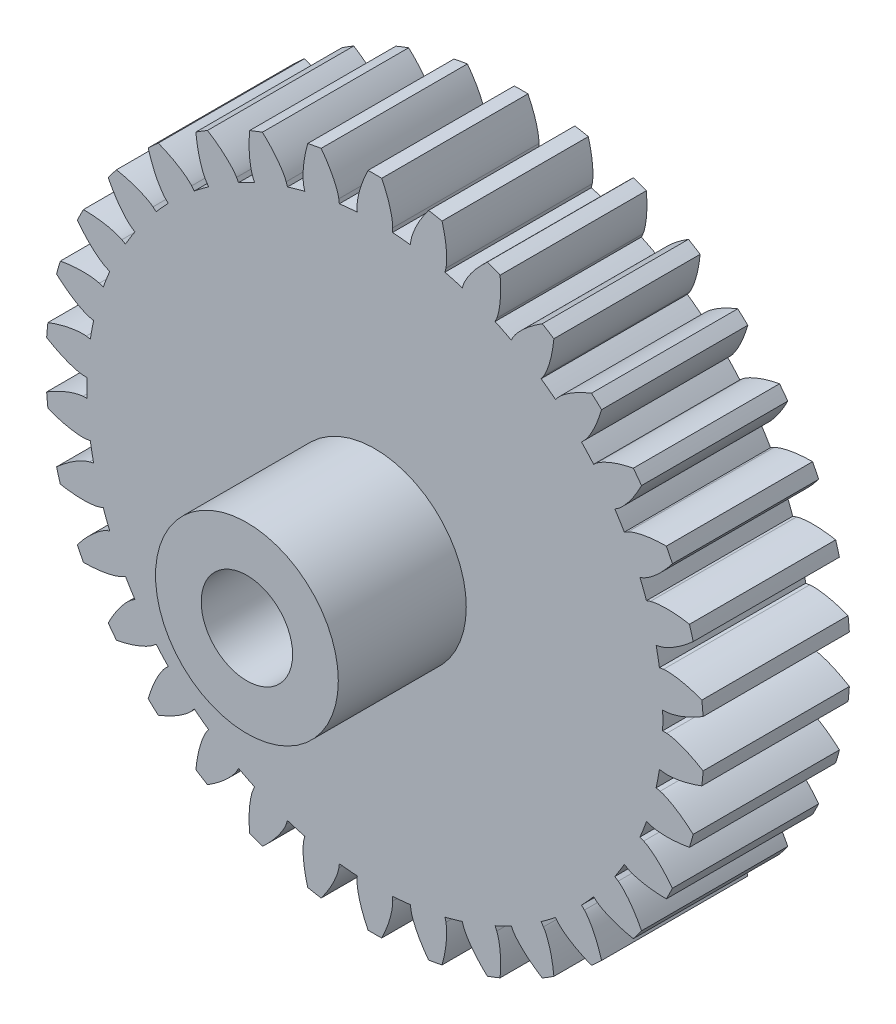
SolidWorks part; units mm, degrees
ref_plane "Płaszczyzna przednia" through (0, 0, 0) normal (0, 0, 1) x (1, 0, 0)
ref_plane "Płaszczyzna górna" through (0, 0, 0) normal (0, 1, 0) x (1, 0, 0)
ref_plane "Płaszczyzna prawa" through (0, 0, 0) normal (1, 0, 0) x (0, 0, -1)
sketch "Szkic1" plane through (0, 0, 0) normal (0, 0, 1) x (1, 0, 0)
  circle A0 centre (0, 0) radius 18
extrude "Dodanie-wyciągnięcie1" add sketch "Szkic1" along normal blind 8
sketch "Szkic2" plane through (0, 0, 8) normal (0, 0, 1) x (1, 0, 0)
  circle A0 centre (0, 0) radius 5
extrude "Dodanie-wyciągnięcie2" add sketch "Szkic2" along normal blind 7
sketch "Szkic3" plane through (0, 0, 15) normal (0, 0, 1) x (1, 0, 0)
  circle A0 centre (0, 0) radius 2.5
extrude "Wytnij-wyciągnięcie1" cut sketch "Szkic3" against normal through all
sketch "Szkic4" plane through (0, 0, 0) normal (0, 0, -1) x (-1, 0, 0)
  line L0 (15.967, 0.4999) -> (15.7423, 0.4928)
  line L1 (15.7423, -0.4928) -> (15.967, -0.4999)
  line L2 (15.3837, -3.3771) -> (15.6032, -3.4253)
  line L3 (14.5012, -6.1463) -> (14.7082, -6.234)
  line L4 (13.1249, -8.7063) -> (13.3122, -8.8305)
  line L5 (11.3017, -10.9697) -> (11.463, -11.1263)
  line L6 (9.0936, -12.8596) -> (9.2233, -13.0431)
  line L7 (6.5758, -14.3116) -> (6.6696, -14.5158)
  line L8 (3.8341, -15.2762) -> (3.8888, -15.4942)
  line L9 (0.9618, -15.7206) -> (0.9755, -15.945)
  line L10 (-1.9432, -15.6297) -> (-1.971, -15.8527)
  line L11 (-4.7821, -15.0065) -> (-4.8503, -15.2206)
  line L12 (-7.4581, -13.8722) -> (-7.5645, -14.0702)
  line L13 (-9.8801, -12.2656) -> (-10.0211, -12.4407)
  line L14 (-11.9657, -10.2413) -> (-12.1365, -10.3875)
  line L15 (-13.6438, -7.8682) -> (-13.8385, -7.9805)
  line L16 (-14.8573, -5.2272) -> (-15.0693, -5.3018)
  line L17 (-15.5648, -2.4082) -> (-15.7869, -2.4426)
  line L18 (-15.7423, 0.4928) -> (-15.967, 0.4999)
  line L19 (-15.3837, 3.3771) -> (-15.6032, 3.4253)
  line L20 (-14.5012, 6.1463) -> (-14.7082, 6.234)
  line L21 (-13.1249, 8.7063) -> (-13.3122, 8.8305)
  line L22 (-11.3017, 10.9697) -> (-11.463, 11.1263)
  line L23 (-9.0936, 12.8596) -> (-9.2233, 13.0431)
  line L24 (-6.5758, 14.3116) -> (-6.6696, 14.5158)
  line L25 (-3.8341, 15.2762) -> (-3.8888, 15.4942)
  line L26 (-0.9618, 15.7206) -> (-0.9755, 15.945)
  line L27 (1.9432, 15.6297) -> (1.971, 15.8527)
  line L28 (4.7821, 15.0065) -> (4.8503, 15.2206)
  line L29 (7.4581, 13.8722) -> (7.5645, 14.0702)
  line L30 (9.8801, 12.2656) -> (10.0211, 12.4407)
  line L31 (11.9657, 10.2413) -> (12.1365, 10.3875)
  line L32 (13.6438, 7.8682) -> (13.8385, 7.9805)
  line L33 (14.8573, 5.2272) -> (15.0693, 5.3018)
  line L34 (15.5648, 2.4082) -> (15.7869, 2.4426)
  line L35 (15.7869, -2.4426) -> (15.5648, -2.4082)
  line L36 (15.0693, -5.3018) -> (14.8573, -5.2272)
  line L37 (13.8385, -7.9805) -> (13.6438, -7.8682)
  line L38 (12.1365, -10.3875) -> (11.9657, -10.2413)
  line L39 (10.0211, -12.4407) -> (9.8801, -12.2656)
  line L40 (7.5645, -14.0702) -> (7.4581, -13.8722)
  line L41 (4.8503, -15.2206) -> (4.7821, -15.0065)
  line L42 (1.971, -15.8527) -> (1.9432, -15.6297)
  line L43 (-0.9755, -15.945) -> (-0.9618, -15.7206)
  line L44 (-3.8888, -15.4942) -> (-3.8341, -15.2762)
  line L45 (-6.6696, -14.5158) -> (-6.5758, -14.3116)
  line L46 (-9.2233, -13.0431) -> (-9.0936, -12.8596)
  line L47 (-11.463, -11.1263) -> (-11.3017, -10.9697)
  line L48 (-13.3122, -8.8305) -> (-13.1249, -8.7063)
  line L49 (-14.7082, -6.234) -> (-14.5012, -6.1463)
  line L50 (-15.6032, -3.4253) -> (-15.3837, -3.3771)
  line L51 (-15.967, -0.4999) -> (-15.7423, -0.4928)
  line L52 (-15.7869, 2.4426) -> (-15.5648, 2.4082)
  line L53 (-15.0693, 5.3018) -> (-14.8573, 5.2272)
  line L54 (-13.8385, 7.9805) -> (-13.6438, 7.8682)
  line L55 (-12.1365, 10.3875) -> (-11.9657, 10.2413)
  line L56 (-10.0211, 12.4407) -> (-9.8801, 12.2656)
  line L57 (-7.5645, 14.0702) -> (-7.4581, 13.8722)
  line L58 (-4.8503, 15.2206) -> (-4.7821, 15.0065)
  line L59 (-1.971, 15.8527) -> (-1.9432, 15.6297)
  line L60 (0.9755, 15.945) -> (0.9618, 15.7206)
  line L61 (3.8888, 15.4942) -> (3.8341, 15.2762)
  line L62 (6.6696, 14.5158) -> (6.5758, 14.3116)
  line L63 (9.2233, 13.0431) -> (9.0936, 12.8596)
  line L64 (11.463, 11.1263) -> (11.3017, 10.9697)
  line L65 (13.3122, 8.8305) -> (13.1249, 8.7063)
  line L66 (14.7082, 6.234) -> (14.5012, 6.1463)
  line L67 (15.6032, 3.4253) -> (15.3837, 3.3771)
  circle A1 centre (0, 0) radius 18
  arc A2 (15.7423, -0.4928) -> (15.7423, 0.4928) centre (0, 0) ccw
  arc A4 (15.3837, -3.3771) -> (15.5648, -2.4082) centre (0, 0) ccw
  arc A5 (14.5012, -6.1463) -> (14.8573, -5.2272) centre (0, 0) ccw
  arc A6 (13.1249, -8.7063) -> (13.6438, -7.8682) centre (0, 0) ccw
  arc A7 (11.3017, -10.9697) -> (11.9657, -10.2413) centre (0, 0) ccw
  arc A8 (9.0936, -12.8596) -> (9.8801, -12.2656) centre (0, 0) ccw
  arc A9 (6.5758, -14.3116) -> (7.4581, -13.8722) centre (0, 0) ccw
  arc A10 (3.8341, -15.2762) -> (4.7821, -15.0065) centre (0, 0) ccw
  arc A11 (0.9618, -15.7206) -> (1.9432, -15.6297) centre (0, 0) ccw
  arc A12 (-1.9432, -15.6297) -> (-0.9618, -15.7206) centre (0, 0) ccw
  arc A13 (-4.7821, -15.0065) -> (-3.8341, -15.2762) centre (0, 0) ccw
  arc A14 (-7.4581, -13.8722) -> (-6.5758, -14.3116) centre (0, 0) ccw
  arc A15 (-9.8801, -12.2656) -> (-9.0936, -12.8596) centre (0, 0) ccw
  arc A16 (-11.9657, -10.2413) -> (-11.3017, -10.9697) centre (0, 0) ccw
  arc A17 (-13.6438, -7.8682) -> (-13.1249, -8.7063) centre (0, 0) ccw
  arc A18 (-14.8573, -5.2272) -> (-14.5012, -6.1463) centre (0, 0) ccw
  arc A19 (-15.5648, -2.4082) -> (-15.3837, -3.3771) centre (0, 0) ccw
  arc A20 (-15.7423, 0.4928) -> (-15.7423, -0.4928) centre (0, 0) ccw
  arc A21 (-15.3837, 3.3771) -> (-15.5648, 2.4082) centre (0, 0) ccw
  arc A22 (-14.5012, 6.1463) -> (-14.8573, 5.2272) centre (0, 0) ccw
  arc A23 (-13.1249, 8.7063) -> (-13.6438, 7.8682) centre (0, 0) ccw
  arc A24 (-11.3017, 10.9697) -> (-11.9657, 10.2413) centre (0, 0) ccw
  arc A25 (-9.0936, 12.8596) -> (-9.8801, 12.2656) centre (0, 0) ccw
  arc A26 (-6.5758, 14.3116) -> (-7.4581, 13.8722) centre (0, 0) ccw
  arc A27 (-3.8341, 15.2762) -> (-4.7821, 15.0065) centre (0, 0) ccw
  arc A28 (-0.9618, 15.7206) -> (-1.9432, 15.6297) centre (0, 0) ccw
  arc A29 (1.9432, 15.6297) -> (0.9618, 15.7206) centre (0, 0) ccw
  arc A30 (4.7821, 15.0065) -> (3.8341, 15.2762) centre (0, 0) ccw
  arc A31 (7.4581, 13.8722) -> (6.5758, 14.3116) centre (0, 0) ccw
  arc A32 (9.8801, 12.2656) -> (9.0936, 12.8596) centre (0, 0) ccw
  arc A33 (11.9657, 10.2413) -> (11.3017, 10.9697) centre (0, 0) ccw
  arc A34 (13.6438, 7.8682) -> (13.1249, 8.7063) centre (0, 0) ccw
  arc A35 (14.8573, 5.2272) -> (14.5012, 6.1463) centre (0, 0) ccw
  arc A36 (15.5648, 2.4082) -> (15.3837, 3.3771) centre (0, 0) ccw
  spline S0 degree 4 poles (15.967, -0.4999) (15.9736, -0.5002) (15.9922, -0.5014) (16.0273, -0.5049) (16.0844, -0.5126) (16.1568, -0.525) (16.2501, -0.5441) (16.3593, -0.5705) (16.4786, -0.6036) (16.6076, -0.6441) (16.7354, -0.6883) (16.862, -0.736) (16.9874, -0.7867) (17.1381, -0.8519) (17.3174, -0.9353) (17.5245, -1.0403) (17.7565, -1.1683) (17.9894, -1.308) (18.2157, -1.4531) (18.4407, -1.6083) (18.6558, -1.7646) (18.8752, -1.9356) (19.0758, -2.0978) (19.2957, -2.2889) (19.4718, -2.4459) (19.6988, -2.6628) (19.8313, -2.7938) (19.9845, -2.9504) (20.0515, -3.0217) (20.0928, -3.0655) knots 0 0 0 0 0 0.005377 0.015084 0.028532 0.04661 0.064855 0.092111 0.119476 0.146842 0.174209 0.201575 0.228941 0.256307 0.307035 0.361767 0.4165 0.471232 0.525964 0.580697 0.635429 0.690161 0.744894 0.799626 0.854358 0.909091 0.954545 1 1 1 1 1 construction
  spline S1 degree 4 poles (15.967, -0.4999) (15.9736, -0.5002) (15.9922, -0.5014) (16.0273, -0.5049) (16.0844, -0.5126) (16.1568, -0.525) (16.2501, -0.5441) (16.3593, -0.5705) (16.4786, -0.6036) (16.6076, -0.6441) (16.7354, -0.6883) (16.862, -0.736) (16.9874, -0.7867) (17.1381, -0.8519) (17.3174, -0.9353) (17.5245, -1.0403) (17.7565, -1.1683) (17.9894, -1.308) (18.2157, -1.4531) (18.4407, -1.6083) (18.6558, -1.7646) (18.8752, -1.9356) (19.0758, -2.0978) (19.2957, -2.2889) (19.4718, -2.4459) (19.6496, -2.6158) (19.7355, -2.6996) (19.7792, -2.7428) knots 0 0 0 0 0 0.005377 0.015084 0.028532 0.04661 0.064855 0.092111 0.119476 0.146842 0.174209 0.201575 0.228941 0.256307 0.307035 0.361767 0.4165 0.471232 0.525964 0.580697 0.635429 0.690161 0.744894 0.799626 0.854358 0.909091 0.909091 0.909091 0.909091 0.909091
  spline S2 degree 4 poles (15.967, 0.4999) (15.9736, 0.5002) (15.9922, 0.5014) (16.0273, 0.5049) (16.0844, 0.5126) (16.1568, 0.525) (16.2501, 0.5441) (16.3593, 0.5705) (16.4786, 0.6036) (16.6076, 0.6441) (16.7354, 0.6883) (16.862, 0.736) (16.9874, 0.7867) (17.1381, 0.8519) (17.3174, 0.9353) (17.5245, 1.0403) (17.7565, 1.1683) (17.9894, 1.308) (18.2157, 1.4531) (18.4407, 1.6083) (18.6558, 1.7646) (18.8752, 1.9356) (19.0758, 2.0978) (19.2957, 2.2889) (19.4718, 2.4459) (19.6988, 2.6628) (19.8313, 2.7938) (19.9845, 2.9504) (20.0515, 3.0217) (20.0928, 3.0655) knots 0 0 0 0 0 0.005377 0.015084 0.028532 0.04661 0.064855 0.092111 0.119476 0.146842 0.174209 0.201575 0.228941 0.256307 0.307035 0.361767 0.4165 0.471232 0.525964 0.580697 0.635429 0.690161 0.744894 0.799626 0.854358 0.909091 0.954545 1 1 1 1 1 construction
  spline S3 degree 4 poles (15.967, 0.4999) (15.9736, 0.5002) (15.9922, 0.5014) (16.0273, 0.5049) (16.0844, 0.5126) (16.1568, 0.525) (16.2501, 0.5441) (16.3593, 0.5705) (16.4786, 0.6036) (16.6076, 0.6441) (16.7354, 0.6883) (16.862, 0.736) (16.9874, 0.7867) (17.1381, 0.8519) (17.3174, 0.9353) (17.5245, 1.0403) (17.7565, 1.1683) (17.9894, 1.308) (18.2157, 1.4531) (18.4407, 1.6083) (18.6558, 1.7646) (18.8752, 1.9356) (19.0758, 2.0978) (19.2957, 2.2889) (19.4718, 2.4459) (19.6496, 2.6158) (19.7355, 2.6996) (19.7792, 2.7428) knots 0 0 0 0 0 0.005377 0.015084 0.028532 0.04661 0.064855 0.092111 0.119476 0.146842 0.174209 0.201575 0.228941 0.256307 0.307035 0.361767 0.4165 0.471232 0.525964 0.580697 0.635429 0.690161 0.744894 0.799626 0.854358 0.909091 0.909091 0.909091 0.909091 0.909091
  spline S4 degree 4 poles (15.7869, -2.4426) (15.7935, -2.4435) (15.812, -2.4457) (15.8472, -2.4487) (15.9047, -2.4516) (15.9782, -2.4528) (16.0733, -2.4511) (16.1856, -2.4452) (16.309, -2.4346) (16.4432, -2.4185) (16.5769, -2.3985) (16.7102, -2.3749) (16.8427, -2.3481) (17.0028, -2.3117) (17.1944, -2.2627) (17.4173, -2.1975) (17.6688, -2.1144) (17.9234, -2.0198) (18.1725, -1.9188) (18.4222, -1.8075) (18.6624, -1.6934) (18.9095, -1.5657) (19.1364, -1.4431) (19.3877, -1.2956) (19.5897, -1.1737) (19.8527, -1.0022) (20.007, -0.8978) (20.1863, -0.772) (20.2653, -0.7142) (20.314, -0.6787) knots 0 0 0 0 0 0.005377 0.015084 0.028532 0.04661 0.064855 0.092111 0.119476 0.146842 0.174209 0.201575 0.228941 0.256307 0.307035 0.361767 0.4165 0.471232 0.525964 0.580697 0.635429 0.690161 0.744894 0.799626 0.854358 0.909091 0.954545 1 1 1 1 1 construction
  spline S5 degree 4 poles (15.7869, -2.4426) (15.7935, -2.4435) (15.812, -2.4457) (15.8472, -2.4487) (15.9047, -2.4516) (15.9782, -2.4528) (16.0733, -2.4511) (16.1856, -2.4452) (16.309, -2.4346) (16.4432, -2.4185) (16.5769, -2.3985) (16.7102, -2.3749) (16.8427, -2.3481) (17.0028, -2.3117) (17.1944, -2.2627) (17.4173, -2.1975) (17.6688, -2.1144) (17.9234, -2.0198) (18.1725, -1.9188) (18.4222, -1.8075) (18.6624, -1.6934) (18.9095, -1.5657) (19.1364, -1.4431) (19.3877, -1.2956) (19.5897, -1.1737) (19.7957, -1.0394) (19.8956, -0.9728) (19.9464, -0.9383) knots 0 0 0 0 0 0.005377 0.015084 0.028532 0.04661 0.064855 0.092111 0.119476 0.146842 0.174209 0.201575 0.228941 0.256307 0.307035 0.361767 0.4165 0.471232 0.525964 0.580697 0.635429 0.690161 0.744894 0.799626 0.854358 0.909091 0.909091 0.909091 0.909091 0.909091
  spline S6 degree 4 poles (15.6032, -3.4253) (15.6097, -3.4268) (15.6278, -3.4314) (15.6616, -3.4413) (15.7163, -3.4593) (15.7852, -3.4849) (15.8734, -3.5208) (15.9759, -3.5668) (16.0871, -3.6213) (16.2065, -3.6848) (16.324, -3.7517) (16.4397, -3.8218) (16.5536, -3.8947) (16.6898, -3.9865) (16.8507, -4.1014) (17.035, -4.2427) (17.2395, -4.4111) (17.4428, -4.5913) (17.6385, -4.7755) (17.8312, -4.9694) (18.0139, -5.1626) (18.1982, -5.3709) (18.3655, -5.5673) (18.5465, -5.7955) (18.6908, -5.9822) (18.8741, -6.2371) (18.9803, -6.3902) (19.1021, -6.5723) (19.1548, -6.6547) (19.1874, -6.7054) knots 0 0 0 0 0 0.005377 0.015084 0.028532 0.04661 0.064855 0.092111 0.119476 0.146842 0.174209 0.201575 0.228941 0.256307 0.307035 0.361767 0.4165 0.471232 0.525964 0.580697 0.635429 0.690161 0.744894 0.799626 0.854358 0.909091 0.954545 1 1 1 1 1 construction
  spline S7 degree 4 poles (15.6032, -3.4253) (15.6097, -3.4268) (15.6278, -3.4314) (15.6616, -3.4413) (15.7163, -3.4593) (15.7852, -3.4849) (15.8734, -3.5208) (15.9759, -3.5668) (16.0871, -3.6213) (16.2065, -3.6848) (16.324, -3.7517) (16.4397, -3.8218) (16.5536, -3.8947) (16.6898, -3.9865) (16.8507, -4.1014) (17.035, -4.2427) (17.2395, -4.4111) (17.4428, -4.5913) (17.6385, -4.7755) (17.8312, -4.9694) (18.0139, -5.1626) (18.1982, -5.3709) (18.3655, -5.5673) (18.5465, -5.7955) (18.6908, -5.9822) (18.8344, -6.1818) (18.9035, -6.28) (18.9384, -6.3306) knots 0 0 0 0 0 0.005377 0.015084 0.028532 0.04661 0.064855 0.092111 0.119476 0.146842 0.174209 0.201575 0.228941 0.256307 0.307035 0.361767 0.4165 0.471232 0.525964 0.580697 0.635429 0.690161 0.744894 0.799626 0.854358 0.909091 0.909091 0.909091 0.909091 0.909091
  spline S8 degree 4 poles (15.0693, -5.3018) (15.0756, -5.3039) (15.0934, -5.3095) (15.1274, -5.3189) (15.1834, -5.3324) (15.2554, -5.347) (15.3493, -5.3628) (15.4607, -5.3777) (15.5839, -5.3899) (15.7188, -5.3988) (15.8539, -5.4037) (15.9893, -5.405) (16.1244, -5.403) (16.2886, -5.3966) (16.4858, -5.3836) (16.7169, -5.3605) (16.9794, -5.325) (17.2471, -5.2789) (17.5105, -5.2253) (17.7764, -5.1618) (18.0335, -5.0938) (18.2999, -5.0136) (18.5454, -4.9348) (18.8195, -4.836) (19.0405, -4.7533) (19.3305, -4.6331) (19.5014, -4.5588) (19.7008, -4.4681) (19.789, -4.4258) (19.8434, -4.3998) knots 0 0 0 0 0 0.005377 0.015084 0.028532 0.04661 0.064855 0.092111 0.119476 0.146842 0.174209 0.201575 0.228941 0.256307 0.307035 0.361767 0.4165 0.471232 0.525964 0.580697 0.635429 0.690161 0.744894 0.799626 0.854358 0.909091 0.954545 1 1 1 1 1 construction
  spline S9 degree 4 poles (15.0693, -5.3018) (15.0756, -5.3039) (15.0934, -5.3095) (15.1274, -5.3189) (15.1834, -5.3324) (15.2554, -5.347) (15.3493, -5.3628) (15.4607, -5.3777) (15.5839, -5.3899) (15.7188, -5.3988) (15.8539, -5.4037) (15.9893, -5.405) (16.1244, -5.403) (16.2886, -5.3966) (16.4858, -5.3836) (16.7169, -5.3605) (16.9794, -5.325) (17.2471, -5.2789) (17.5105, -5.2253) (17.7764, -5.1618) (18.0335, -5.0938) (18.2999, -5.0136) (18.5454, -4.9348) (18.8195, -4.836) (19.0405, -4.7533) (19.2676, -4.6591) (19.378, -4.612) (19.4344, -4.5874) knots 0 0 0 0 0 0.005377 0.015084 0.028532 0.04661 0.064855 0.092111 0.119476 0.146842 0.174209 0.201575 0.228941 0.256307 0.307035 0.361767 0.4165 0.471232 0.525964 0.580697 0.635429 0.690161 0.744894 0.799626 0.854358 0.909091 0.909091 0.909091 0.909091 0.909091
  spline S10 degree 4 poles (14.7082, -6.234) (14.7142, -6.2367) (14.7312, -6.2446) (14.7626, -6.2606) (14.8131, -6.2883) (14.8761, -6.3261) (14.9562, -6.3775) (15.0485, -6.4417) (15.1478, -6.5157) (15.2535, -6.6) (15.3567, -6.6873) (15.4575, -6.7776) (15.5561, -6.8701) (15.6731, -6.9854) (15.8101, -7.1279) (15.9653, -7.3007) (16.1354, -7.5038) (16.3021, -7.7182) (16.4607, -7.9352) (16.6144, -8.1613) (16.7586, -8.3847) (16.9014, -8.6234) (17.0298, -8.8471) (17.1658, -9.1048) (17.2734, -9.3148) (17.4067, -9.599) (17.4829, -9.769) (17.5692, -9.9704) (17.6059, -10.0611) (17.6286, -10.1169) knots 0 0 0 0 0 0.005377 0.015084 0.028532 0.04661 0.064855 0.092111 0.119476 0.146842 0.174209 0.201575 0.228941 0.256307 0.307035 0.361767 0.4165 0.471232 0.525964 0.580697 0.635429 0.690161 0.744894 0.799626 0.854358 0.909091 0.954545 1 1 1 1 1 construction
  spline S11 degree 4 poles (14.7082, -6.234) (14.7142, -6.2367) (14.7312, -6.2446) (14.7626, -6.2606) (14.8131, -6.2883) (14.8761, -6.3261) (14.9562, -6.3775) (15.0485, -6.4417) (15.1478, -6.5157) (15.2535, -6.6) (15.3567, -6.6873) (15.4575, -6.7776) (15.5561, -6.8701) (15.6731, -6.9854) (15.8101, -7.1279) (15.9653, -7.3007) (16.1354, -7.5038) (16.3021, -7.7182) (16.4607, -7.9352) (16.6144, -8.1613) (16.7586, -8.3847) (16.9014, -8.6234) (17.0298, -8.8471) (17.1658, -9.1048) (17.2734, -9.3148) (17.3778, -9.5374) (17.4277, -9.6466) (17.4527, -9.7027) knots 0 0 0 0 0 0.005377 0.015084 0.028532 0.04661 0.064855 0.092111 0.119476 0.146842 0.174209 0.201575 0.228941 0.256307 0.307035 0.361767 0.4165 0.471232 0.525964 0.580697 0.635429 0.690161 0.744894 0.799626 0.854358 0.909091 0.909091 0.909091 0.909091 0.909091
  spline S12 degree 4 poles (13.8385, -7.9805) (13.8443, -7.9838) (13.8608, -7.9925) (13.8925, -8.008) (13.945, -8.0315) (14.0132, -8.0591) (14.1025, -8.092) (14.2093, -8.127) (14.3282, -8.1617) (14.4591, -8.1952) (14.5911, -8.2249) (14.7238, -8.251) (14.8571, -8.2738) (15.0196, -8.2978) (15.2159, -8.3212) (15.4473, -8.341) (15.7119, -8.3543) (15.9835, -8.3581) (16.2522, -8.3539) (16.5253, -8.3403) (16.7904, -8.3207) (17.067, -8.2909) (17.3229, -8.2585) (17.6105, -8.2118) (17.8429, -8.171) (18.1501, -8.1062) (18.3317, -8.0645) (18.5443, -8.012) (18.6388, -7.9867) (18.697, -7.9711) knots 0 0 0 0 0 0.005377 0.015084 0.028532 0.04661 0.064855 0.092111 0.119476 0.146842 0.174209 0.201575 0.228941 0.256307 0.307035 0.361767 0.4165 0.471232 0.525964 0.580697 0.635429 0.690161 0.744894 0.799626 0.854358 0.909091 0.954545 1 1 1 1 1 construction
  spline S13 degree 4 poles (13.8385, -7.9805) (13.8443, -7.9838) (13.8608, -7.9925) (13.8925, -8.008) (13.945, -8.0315) (14.0132, -8.0591) (14.1025, -8.092) (14.2093, -8.127) (14.3282, -8.1617) (14.4591, -8.1952) (14.5911, -8.2249) (14.7238, -8.251) (14.8571, -8.2738) (15.0196, -8.2978) (15.2159, -8.3212) (15.4473, -8.341) (15.7119, -8.3543) (15.9835, -8.3581) (16.2522, -8.3539) (16.5253, -8.3403) (16.7904, -8.3207) (17.067, -8.2909) (17.3229, -8.2585) (17.6105, -8.2118) (17.8429, -8.171) (18.0835, -8.1202) (18.2006, -8.0942) (18.2605, -8.0804) knots 0 0 0 0 0 0.005377 0.015084 0.028532 0.04661 0.064855 0.092111 0.119476 0.146842 0.174209 0.201575 0.228941 0.256307 0.307035 0.361767 0.4165 0.471232 0.525964 0.580697 0.635429 0.690161 0.744894 0.799626 0.854358 0.909091 0.909091 0.909091 0.909091 0.909091
  spline S14 degree 4 poles (13.3122, -8.8305) (13.3177, -8.8343) (13.3329, -8.8451) (13.3608, -8.8666) (13.4054, -8.9031) (13.4604, -8.9518) (13.5296, -9.0171) (13.6086, -9.0971) (13.6926, -9.1881) (13.781, -9.2904) (13.8664, -9.3953) (13.949, -9.5025) (14.0288, -9.6116) (14.1227, -9.7463) (14.2312, -9.9116) (14.352, -10.11) (14.4818, -10.3409) (14.6063, -10.5823) (14.7223, -10.8248) (14.8319, -11.0752) (14.9325, -11.3213) (15.0291, -11.5822) (15.1142, -11.8257) (15.2006, -12.104) (15.2677, -12.3302) (15.3465, -12.634) (15.3902, -12.8152) (15.438, -13.0289) (15.4574, -13.1248) (15.4694, -13.1839) knots 0 0 0 0 0 0.005377 0.015084 0.028532 0.04661 0.064855 0.092111 0.119476 0.146842 0.174209 0.201575 0.228941 0.256307 0.307035 0.361767 0.4165 0.471232 0.525964 0.580697 0.635429 0.690161 0.744894 0.799626 0.854358 0.909091 0.954545 1 1 1 1 1 construction
  spline S15 degree 4 poles (13.3122, -8.8305) (13.3177, -8.8343) (13.3329, -8.8451) (13.3608, -8.8666) (13.4054, -8.9031) (13.4604, -8.9518) (13.5296, -9.0171) (13.6086, -9.0971) (13.6926, -9.1881) (13.781, -9.2904) (13.8664, -9.3953) (13.949, -9.5025) (14.0288, -9.6116) (14.1227, -9.7463) (14.2312, -9.9116) (14.352, -10.11) (14.4818, -10.3409) (14.6063, -10.5823) (14.7223, -10.8248) (14.8319, -11.0752) (14.9325, -11.3213) (15.0291, -11.5822) (15.1142, -11.8257) (15.2006, -12.104) (15.2677, -12.3302) (15.3294, -12.5682) (15.3584, -12.6846) (15.3727, -12.7444) knots 0 0 0 0 0 0.005377 0.015084 0.028532 0.04661 0.064855 0.092111 0.119476 0.146842 0.174209 0.201575 0.228941 0.256307 0.307035 0.361767 0.4165 0.471232 0.525964 0.580697 0.635429 0.690161 0.744894 0.799626 0.854358 0.909091 0.909091 0.909091 0.909091 0.909091
  spline S16 degree 4 poles (12.1365, -10.3875) (12.1416, -10.3917) (12.1561, -10.4033) (12.1845, -10.4243) (12.2318, -10.4572) (12.2937, -10.4968) (12.3755, -10.5455) (12.474, -10.5996) (12.5845, -10.6555) (12.7071, -10.7125) (12.8313, -10.7659) (12.957, -10.816) (13.0838, -10.8629) (13.2391, -10.9163) (13.4278, -10.9755) (13.6516, -11.0374) (13.9092, -11.0991) (14.1755, -11.1528) (14.4405, -11.198) (14.7114, -11.2348) (14.9756, -11.2643) (15.253, -11.2857) (15.5104, -11.301) (15.8017, -11.3079) (16.0376, -11.3105) (16.3515, -11.3032) (16.5377, -11.2957) (16.7564, -11.2831) (16.8539, -11.2755) (16.914, -11.271) knots 0 0 0 0 0 0.005377 0.015084 0.028532 0.04661 0.064855 0.092111 0.119476 0.146842 0.174209 0.201575 0.228941 0.256307 0.307035 0.361767 0.4165 0.471232 0.525964 0.580697 0.635429 0.690161 0.744894 0.799626 0.854358 0.909091 0.954545 1 1 1 1 1 construction
  spline S17 degree 4 poles (12.1365, -10.3875) (12.1416, -10.3917) (12.1561, -10.4033) (12.1845, -10.4243) (12.2318, -10.4572) (12.2937, -10.4968) (12.3755, -10.5455) (12.474, -10.5996) (12.5845, -10.6555) (12.7071, -10.7125) (12.8313, -10.7659) (12.957, -10.816) (13.0838, -10.8629) (13.2391, -10.9163) (13.4278, -10.9755) (13.6516, -11.0374) (13.9092, -11.0991) (14.1755, -11.1528) (14.4405, -11.198) (14.7114, -11.2348) (14.9756, -11.2643) (15.253, -11.2857) (15.5104, -11.301) (15.8017, -11.3079) (16.0376, -11.3105) (16.2835, -11.3048) (16.4034, -11.3008) (16.4648, -11.2982) knots 0 0 0 0 0 0.005377 0.015084 0.028532 0.04661 0.064855 0.092111 0.119476 0.146842 0.174209 0.201575 0.228941 0.256307 0.307035 0.361767 0.4165 0.471232 0.525964 0.580697 0.635429 0.690161 0.744894 0.799626 0.854358 0.909091 0.909091 0.909091 0.909091 0.909091
  spline S18 degree 4 poles (11.463, -11.1263) (11.4677, -11.131) (11.4806, -11.1444) (11.5041, -11.1707) (11.5412, -11.2148) (11.5863, -11.2727) (11.6424, -11.3497) (11.7053, -11.4428) (11.7712, -11.5477) (11.8392, -11.6645) (11.9039, -11.7832) (11.9654, -11.9038) (12.0238, -12.0257) (12.0913, -12.1754) (12.1676, -12.3578) (12.2499, -12.575) (12.3351, -12.8258) (12.4131, -13.086) (12.4826, -13.3457) (12.5443, -13.612) (12.598, -13.8724) (12.645, -14.1466) (12.6839, -14.4016) (12.7176, -14.691) (12.742, -14.9256) (12.7637, -15.2388) (12.7734, -15.4249) (12.781, -15.6438) (12.7825, -15.7417) (12.7835, -15.8019) knots 0 0 0 0 0 0.005377 0.015084 0.028532 0.04661 0.064855 0.092111 0.119476 0.146842 0.174209 0.201575 0.228941 0.256307 0.307035 0.361767 0.4165 0.471232 0.525964 0.580697 0.635429 0.690161 0.744894 0.799626 0.854358 0.909091 0.954545 1 1 1 1 1 construction
  spline S19 degree 4 poles (11.463, -11.1263) (11.4677, -11.131) (11.4806, -11.1444) (11.5041, -11.1707) (11.5412, -11.2148) (11.5863, -11.2727) (11.6424, -11.3497) (11.7053, -11.4428) (11.7712, -11.5477) (11.8392, -11.6645) (11.9039, -11.7832) (11.9654, -11.9038) (12.0238, -12.0257) (12.0913, -12.1754) (12.1676, -12.3578) (12.2499, -12.575) (12.3351, -12.8258) (12.4131, -13.086) (12.4826, -13.3457) (12.5443, -13.612) (12.598, -13.8724) (12.645, -14.1466) (12.6839, -14.4016) (12.7176, -14.691) (12.742, -14.9256) (12.759, -15.1709) (12.7661, -15.2907) (12.7692, -15.3521) knots 0 0 0 0 0 0.005377 0.015084 0.028532 0.04661 0.064855 0.092111 0.119476 0.146842 0.174209 0.201575 0.228941 0.256307 0.307035 0.361767 0.4165 0.471232 0.525964 0.580697 0.635429 0.690161 0.744894 0.799626 0.854358 0.909091 0.909091 0.909091 0.909091 0.909091
  spline S20 degree 4 poles (10.0211, -12.4407) (10.0254, -12.4458) (10.0376, -12.4599) (10.0615, -12.4857) (10.102, -12.5267) (10.1556, -12.577) (10.227, -12.6399) (10.314, -12.7112) (10.4123, -12.7865) (10.5223, -12.865) (10.6346, -12.9404) (10.749, -13.0127) (10.865, -13.0821) (11.0078, -13.1631) (11.1824, -13.2559) (11.3911, -13.3579) (11.633, -13.4659) (11.8848, -13.5676) (12.137, -13.6607) (12.3965, -13.7468) (12.6508, -13.8242) (12.9195, -13.8963) (13.1698, -13.9586) (13.4549, -14.0189) (13.6863, -14.0648) (13.9962, -14.1153) (14.1805, -14.1421) (14.3978, -14.17) (14.4951, -14.1805) (14.555, -14.187) knots 0 0 0 0 0 0.005377 0.015084 0.028532 0.04661 0.064855 0.092111 0.119476 0.146842 0.174209 0.201575 0.228941 0.256307 0.307035 0.361767 0.4165 0.471232 0.525964 0.580697 0.635429 0.690161 0.744894 0.799626 0.854358 0.909091 0.954545 1 1 1 1 1 construction
  spline S21 degree 4 poles (10.0211, -12.4407) (10.0254, -12.4458) (10.0376, -12.4599) (10.0615, -12.4857) (10.102, -12.5267) (10.1556, -12.577) (10.227, -12.6399) (10.314, -12.7112) (10.4123, -12.7865) (10.5223, -12.865) (10.6346, -12.9404) (10.749, -13.0127) (10.865, -13.0821) (11.0078, -13.1631) (11.1824, -13.2559) (11.3911, -13.3579) (11.633, -13.4659) (11.8848, -13.5676) (12.137, -13.6607) (12.3965, -13.7468) (12.6508, -13.8242) (12.9195, -13.8963) (13.1698, -13.9586) (13.4549, -14.0189) (13.6863, -14.0648) (13.929, -14.1044) (14.0476, -14.1225) (14.1085, -14.1312) knots 0 0 0 0 0 0.005377 0.015084 0.028532 0.04661 0.064855 0.092111 0.119476 0.146842 0.174209 0.201575 0.228941 0.256307 0.307035 0.361767 0.4165 0.471232 0.525964 0.580697 0.635429 0.690161 0.744894 0.799626 0.854358 0.909091 0.909091 0.909091 0.909091 0.909091
  spline S22 degree 4 poles (9.2233, -13.0431) (9.2271, -13.0486) (9.2373, -13.0642) (9.2556, -13.0943) (9.2839, -13.1445) (9.3177, -13.2098) (9.3587, -13.2957) (9.4034, -13.3988) (9.4489, -13.514) (9.4943, -13.6413) (9.5361, -13.7699) (9.5743, -13.8997) (9.6094, -14.0303) (9.6482, -14.1899) (9.6897, -14.3832) (9.7307, -14.6118) (9.7684, -14.874) (9.7972, -15.1441) (9.8178, -15.4121) (9.8295, -15.6852) (9.8344, -15.9511) (9.8302, -16.2292) (9.8216, -16.487) (9.8016, -16.7777) (9.7825, -17.0128) (9.7463, -17.3247) (9.7216, -17.5094) (9.6889, -17.726) (9.6724, -17.8224) (9.6623, -17.8818) knots 0 0 0 0 0 0.005377 0.015084 0.028532 0.04661 0.064855 0.092111 0.119476 0.146842 0.174209 0.201575 0.228941 0.256307 0.307035 0.361767 0.4165 0.471232 0.525964 0.580697 0.635429 0.690161 0.744894 0.799626 0.854358 0.909091 0.954545 1 1 1 1 1 construction
  spline S23 degree 4 poles (9.2233, -13.0431) (9.2271, -13.0486) (9.2373, -13.0642) (9.2556, -13.0943) (9.2839, -13.1445) (9.3177, -13.2098) (9.3587, -13.2957) (9.4034, -13.3988) (9.4489, -13.514) (9.4943, -13.6413) (9.5361, -13.7699) (9.5743, -13.8997) (9.6094, -14.0303) (9.6482, -14.1899) (9.6897, -14.3832) (9.7307, -14.6118) (9.7684, -14.874) (9.7972, -15.1441) (9.8178, -15.4121) (9.8295, -15.6852) (9.8344, -15.9511) (9.8302, -16.2292) (9.8216, -16.487) (9.8016, -16.7777) (9.7825, -17.0128) (9.7541, -17.2571) (9.739, -17.3761) (9.7308, -17.4371) knots 0 0 0 0 0 0.005377 0.015084 0.028532 0.04661 0.064855 0.092111 0.119476 0.146842 0.174209 0.201575 0.228941 0.256307 0.307035 0.361767 0.4165 0.471232 0.525964 0.580697 0.635429 0.690161 0.744894 0.799626 0.854358 0.909091 0.909091 0.909091 0.909091 0.909091
  spline S24 degree 4 poles (7.5645, -14.0702) (7.5678, -14.076) (7.5771, -14.0921) (7.596, -14.122) (7.6283, -14.1696) (7.6717, -14.229) (7.7303, -14.3039) (7.8027, -14.3899) (7.8855, -14.482) (7.9792, -14.5794) (8.0758, -14.6741) (8.1749, -14.7662) (8.2761, -14.8558) (8.4017, -14.9617) (8.5563, -15.085) (8.7426, -15.2236) (8.9605, -15.3742) (9.1894, -15.5204) (9.4202, -15.6583) (9.6594, -15.7905) (9.8952, -15.9134) (10.1461, -16.0337) (10.3807, -16.1408) (10.6498, -16.2525) (10.8688, -16.3402) (11.1642, -16.4468) (11.3405, -16.507) (11.5489, -16.5743) (11.6426, -16.6025) (11.7003, -16.6199) knots 0 0 0 0 0 0.005377 0.015084 0.028532 0.04661 0.064855 0.092111 0.119476 0.146842 0.174209 0.201575 0.228941 0.256307 0.307035 0.361767 0.4165 0.471232 0.525964 0.580697 0.635429 0.690161 0.744894 0.799626 0.854358 0.909091 0.954545 1 1 1 1 1 construction
  spline S25 degree 4 poles (7.5645, -14.0702) (7.5678, -14.076) (7.5771, -14.0921) (7.596, -14.122) (7.6283, -14.1696) (7.6717, -14.229) (7.7303, -14.3039) (7.8027, -14.3899) (7.8855, -14.482) (7.9792, -14.5794) (8.0758, -14.6741) (8.1749, -14.7662) (8.2761, -14.8558) (8.4017, -14.9617) (8.5563, -15.085) (8.7426, -15.2236) (8.9605, -15.3742) (9.1894, -15.5204) (9.4202, -15.6583) (9.6594, -15.7905) (9.8952, -15.9134) (10.1461, -16.0337) (10.3807, -16.1408) (10.6498, -16.2525) (10.8688, -16.3402) (11.1001, -16.4237) (11.2134, -16.4632) (11.2716, -16.483) knots 0 0 0 0 0 0.005377 0.015084 0.028532 0.04661 0.064855 0.092111 0.119476 0.146842 0.174209 0.201575 0.228941 0.256307 0.307035 0.361767 0.4165 0.471232 0.525964 0.580697 0.635429 0.690161 0.744894 0.799626 0.854358 0.909091 0.909091 0.909091 0.909091 0.909091
  spline S26 degree 4 poles (6.6696, -14.5158) (6.6723, -14.5219) (6.6795, -14.5391) (6.692, -14.5721) (6.7106, -14.6266) (6.7318, -14.697) (6.7562, -14.789) (6.7813, -14.8985) (6.8048, -15.0201) (6.8261, -15.1536) (6.8435, -15.2877) (6.8572, -15.4223) (6.8677, -15.5571) (6.8765, -15.7211) (6.8818, -15.9188) (6.8801, -16.151) (6.8689, -16.4157) (6.8477, -16.6865) (6.8187, -16.9537) (6.78, -17.2243) (6.736, -17.4866) (6.6808, -17.7592) (6.6249, -18.011) (6.5519, -18.2931) (6.4898, -18.5207) (6.3969, -18.8206) (6.3387, -18.9976) (6.2668, -19.2045) (6.2328, -19.2962) (6.212, -19.3528) knots 0 0 0 0 0 0.005377 0.015084 0.028532 0.04661 0.064855 0.092111 0.119476 0.146842 0.174209 0.201575 0.228941 0.256307 0.307035 0.361767 0.4165 0.471232 0.525964 0.580697 0.635429 0.690161 0.744894 0.799626 0.854358 0.909091 0.954545 1 1 1 1 1 construction
  spline S27 degree 4 poles (6.6696, -14.5158) (6.6723, -14.5219) (6.6795, -14.5391) (6.692, -14.5721) (6.7106, -14.6266) (6.7318, -14.697) (6.7562, -14.789) (6.7813, -14.8985) (6.8048, -15.0201) (6.8261, -15.1536) (6.8435, -15.2877) (6.8572, -15.4223) (6.8677, -15.5571) (6.8765, -15.7211) (6.8818, -15.9188) (6.8801, -16.151) (6.8689, -16.4157) (6.8477, -16.6865) (6.8187, -16.9537) (6.78, -17.2243) (6.736, -17.4866) (6.6808, -17.7592) (6.6249, -18.011) (6.5519, -18.2931) (6.4898, -18.5207) (6.4171, -18.7556) (6.3803, -18.8698) (6.3611, -18.9282) knots 0 0 0 0 0 0.005377 0.015084 0.028532 0.04661 0.064855 0.092111 0.119476 0.146842 0.174209 0.201575 0.228941 0.256307 0.307035 0.361767 0.4165 0.471232 0.525964 0.580697 0.635429 0.690161 0.744894 0.799626 0.854358 0.909091 0.909091 0.909091 0.909091 0.909091
  spline S28 degree 4 poles (4.8503, -15.2206) (4.8525, -15.2269) (4.8587, -15.2445) (4.8717, -15.2773) (4.8947, -15.3301) (4.9265, -15.3964) (4.9704, -15.4808) (5.0257, -15.5787) (5.0902, -15.6844) (5.1644, -15.7974) (5.2419, -15.9082) (5.3224, -16.0169) (5.4055, -16.1236) (5.5094, -16.2507) (5.6387, -16.4003) (5.7964, -16.5708) (5.983, -16.7589) (6.1811, -16.9447) (6.3826, -17.1227) (6.5935, -17.2966) (6.8027, -17.4607) (7.0272, -17.625) (7.2381, -17.7735) (7.4821, -17.9327) (7.6813, -18.0591) (7.952, -18.2181) (8.1142, -18.3097) (8.3068, -18.4142) (8.3937, -18.4591) (8.4472, -18.4868) knots 0 0 0 0 0 0.005377 0.015084 0.028532 0.04661 0.064855 0.092111 0.119476 0.146842 0.174209 0.201575 0.228941 0.256307 0.307035 0.361767 0.4165 0.471232 0.525964 0.580697 0.635429 0.690161 0.744894 0.799626 0.854358 0.909091 0.954545 1 1 1 1 1 construction
  spline S29 degree 4 poles (4.8503, -15.2206) (4.8525, -15.2269) (4.8587, -15.2445) (4.8717, -15.2773) (4.8947, -15.3301) (4.9265, -15.3964) (4.9704, -15.4808) (5.0257, -15.5787) (5.0902, -15.6844) (5.1644, -15.7974) (5.2419, -15.9082) (5.3224, -16.0169) (5.4055, -16.1236) (5.5094, -16.2507) (5.6387, -16.4003) (5.7964, -16.5708) (5.983, -16.7589) (6.1811, -16.9447) (6.3826, -17.1227) (6.5935, -17.2966) (6.8027, -17.4607) (7.0272, -17.625) (7.2381, -17.7735) (7.4821, -17.9327) (7.6813, -18.0591) (7.8933, -18.1837) (7.9974, -18.2434) (8.051, -18.2735) knots 0 0 0 0 0 0.005377 0.015084 0.028532 0.04661 0.064855 0.092111 0.119476 0.146842 0.174209 0.201575 0.228941 0.256307 0.307035 0.361767 0.4165 0.471232 0.525964 0.580697 0.635429 0.690161 0.744894 0.799626 0.854358 0.909091 0.909091 0.909091 0.909091 0.909091
  spline S30 degree 4 poles (3.8888, -15.4942) (3.8903, -15.5007) (3.8942, -15.5189) (3.9004, -15.5536) (3.9087, -15.6106) (3.9166, -15.6837) (3.9237, -15.7786) (3.9282, -15.8909) (3.929, -16.0148) (3.9254, -16.1499) (3.9178, -16.2849) (3.9066, -16.4198) (3.8922, -16.5542) (3.8707, -16.717) (3.8395, -16.9123) (3.7952, -17.1402) (3.7356, -17.3983) (3.665, -17.6606) (3.5873, -17.918) (3.4996, -18.1769) (3.4082, -18.4265) (3.3038, -18.6844) (3.2026, -18.9216) (3.079, -19.1855) (2.9762, -19.3978) (2.8297, -19.6756) (2.74, -19.8388) (2.6313, -20.029) (2.581, -20.113) (2.5501, -20.1647) knots 0 0 0 0 0 0.005377 0.015084 0.028532 0.04661 0.064855 0.092111 0.119476 0.146842 0.174209 0.201575 0.228941 0.256307 0.307035 0.361767 0.4165 0.471232 0.525964 0.580697 0.635429 0.690161 0.744894 0.799626 0.854358 0.909091 0.954545 1 1 1 1 1 construction
  spline S31 degree 4 poles (3.8888, -15.4942) (3.8903, -15.5007) (3.8942, -15.5189) (3.9004, -15.5536) (3.9087, -15.6106) (3.9166, -15.6837) (3.9237, -15.7786) (3.9282, -15.8909) (3.929, -16.0148) (3.9254, -16.1499) (3.9178, -16.2849) (3.9066, -16.4198) (3.8922, -16.5542) (3.8707, -16.717) (3.8395, -16.9123) (3.7952, -17.1402) (3.7356, -17.3983) (3.665, -17.6606) (3.5873, -17.918) (3.4996, -18.1769) (3.4082, -18.4265) (3.3038, -18.6844) (3.2026, -18.9216) (3.079, -19.1855) (2.9762, -19.3978) (2.8615, -19.6153) (2.8044, -19.7209) (2.7747, -19.7748) knots 0 0 0 0 0 0.005377 0.015084 0.028532 0.04661 0.064855 0.092111 0.119476 0.146842 0.174209 0.201575 0.228941 0.256307 0.307035 0.361767 0.4165 0.471232 0.525964 0.580697 0.635429 0.690161 0.744894 0.799626 0.854358 0.909091 0.909091 0.909091 0.909091 0.909091
  spline S32 degree 4 poles (1.971, -15.8527) (1.9719, -15.8593) (1.9748, -15.8777) (1.9816, -15.9123) (1.9945, -15.9684) (2.0135, -16.0394) (2.0411, -16.1305) (2.0775, -16.2369) (2.1215, -16.3527) (2.1737, -16.4773) (2.2295, -16.6005) (2.2887, -16.7222) (2.3507, -16.8423) (2.4296, -16.9864) (2.5291, -17.1572) (2.6528, -17.3538) (2.8016, -17.5729) (2.9623, -17.792) (3.1276, -18.0039) (3.303, -18.2136) (3.4784, -18.4134) (3.6689, -18.6161) (3.849, -18.8008) (4.0596, -19.0022) (4.2321, -19.1631) (4.469, -19.3691) (4.6117, -19.489) (4.7817, -19.627) (4.8589, -19.6871) (4.9064, -19.7242) knots 0 0 0 0 0 0.005377 0.015084 0.028532 0.04661 0.064855 0.092111 0.119476 0.146842 0.174209 0.201575 0.228941 0.256307 0.307035 0.361767 0.4165 0.471232 0.525964 0.580697 0.635429 0.690161 0.744894 0.799626 0.854358 0.909091 0.954545 1 1 1 1 1 construction
  spline S33 degree 4 poles (1.971, -15.8527) (1.9719, -15.8593) (1.9748, -15.8777) (1.9816, -15.9123) (1.9945, -15.9684) (2.0135, -16.0394) (2.0411, -16.1305) (2.0775, -16.2369) (2.1215, -16.3527) (2.1737, -16.4773) (2.2295, -16.6005) (2.2887, -16.7222) (2.3507, -16.8423) (2.4296, -16.9864) (2.5291, -17.1572) (2.6528, -17.3538) (2.8016, -17.5729) (2.9623, -17.792) (3.1276, -18.0039) (3.303, -18.2136) (3.4784, -18.4134) (3.6689, -18.6161) (3.849, -18.8008) (4.0596, -19.0022) (4.2321, -19.1631) (4.4176, -19.3244) (4.509, -19.4023) (4.5561, -19.4417) knots 0 0 0 0 0 0.005377 0.015084 0.028532 0.04661 0.064855 0.092111 0.119476 0.146842 0.174209 0.201575 0.228941 0.256307 0.307035 0.361767 0.4165 0.471232 0.525964 0.580697 0.635429 0.690161 0.744894 0.799626 0.854358 0.909091 0.909091 0.909091 0.909091 0.909091
  spline S34 degree 4 poles (0.9755, -15.945) (0.9758, -15.9516) (0.9763, -15.9702) (0.976, -16.0055) (0.9737, -16.063) (0.968, -16.1363) (0.9576, -16.2309) (0.9414, -16.3422) (0.9194, -16.464) (0.891, -16.5962) (0.8588, -16.7275) (0.823, -16.858) (0.7841, -16.9875) (0.7331, -17.1436) (0.6665, -17.3298) (0.5811, -17.5457) (0.4751, -17.7885) (0.3574, -18.0333) (0.2338, -18.2721) (0.1, -18.5104) (-0.0357, -18.739) (-0.1857, -18.9733) (-0.3288, -19.1879) (-0.4988, -19.4246) (-0.6389, -19.6144) (-0.8338, -19.8605) (-0.9521, -20.0045) (-1.0939, -20.1715) (-1.1587, -20.2448) (-1.1985, -20.2899) knots 0 0 0 0 0 0.005377 0.015084 0.028532 0.04661 0.064855 0.092111 0.119476 0.146842 0.174209 0.201575 0.228941 0.256307 0.307035 0.361767 0.4165 0.471232 0.525964 0.580697 0.635429 0.690161 0.744894 0.799626 0.854358 0.909091 0.954545 1 1 1 1 1 construction
  spline S35 degree 4 poles (0.9755, -15.945) (0.9758, -15.9516) (0.9763, -15.9702) (0.976, -16.0055) (0.9737, -16.063) (0.968, -16.1363) (0.9576, -16.2309) (0.9414, -16.3422) (0.9194, -16.464) (0.891, -16.5962) (0.8588, -16.7275) (0.823, -16.858) (0.7841, -16.9875) (0.7331, -17.1436) (0.6665, -17.3298) (0.5811, -17.5457) (0.4751, -17.7885) (0.3574, -18.0333) (0.2338, -18.2721) (0.1, -18.5104) (-0.0357, -18.739) (-0.1857, -18.9733) (-0.3288, -19.1879) (-0.4988, -19.4246) (-0.6389, -19.6144) (-0.7916, -19.8072) (-0.8671, -19.9004) (-0.9061, -19.9479) knots 0 0 0 0 0 0.005377 0.015084 0.028532 0.04661 0.064855 0.092111 0.119476 0.146842 0.174209 0.201575 0.228941 0.256307 0.307035 0.361767 0.4165 0.471232 0.525964 0.580697 0.635429 0.690161 0.744894 0.799626 0.854358 0.909091 0.909091 0.909091 0.909091 0.909091
  spline S36 degree 4 poles (-0.9755, -15.945) (-0.9758, -15.9516) (-0.9763, -15.9702) (-0.976, -16.0055) (-0.9737, -16.063) (-0.968, -16.1363) (-0.9576, -16.2309) (-0.9414, -16.3422) (-0.9194, -16.464) (-0.891, -16.5962) (-0.8588, -16.7275) (-0.823, -16.858) (-0.7841, -16.9875) (-0.7331, -17.1436) (-0.6665, -17.3298) (-0.5811, -17.5457) (-0.4751, -17.7885) (-0.3574, -18.0333) (-0.2338, -18.2721) (-0.1, -18.5104) (0.0357, -18.739) (0.1857, -18.9733) (0.3288, -19.1879) (0.4988, -19.4246) (0.6389, -19.6144) (0.8338, -19.8605) (0.9521, -20.0045) (1.0939, -20.1715) (1.1587, -20.2448) (1.1985, -20.2899) knots 0 0 0 0 0 0.005377 0.015084 0.028532 0.04661 0.064855 0.092111 0.119476 0.146842 0.174209 0.201575 0.228941 0.256307 0.307035 0.361767 0.4165 0.471232 0.525964 0.580697 0.635429 0.690161 0.744894 0.799626 0.854358 0.909091 0.954545 1 1 1 1 1 construction
  spline S37 degree 4 poles (-0.9755, -15.945) (-0.9758, -15.9516) (-0.9763, -15.9702) (-0.976, -16.0055) (-0.9737, -16.063) (-0.968, -16.1363) (-0.9576, -16.2309) (-0.9414, -16.3422) (-0.9194, -16.464) (-0.891, -16.5962) (-0.8588, -16.7275) (-0.823, -16.858) (-0.7841, -16.9875) (-0.7331, -17.1436) (-0.6665, -17.3298) (-0.5811, -17.5457) (-0.4751, -17.7885) (-0.3574, -18.0333) (-0.2338, -18.2721) (-0.1, -18.5104) (0.0357, -18.739) (0.1857, -18.9733) (0.3288, -19.1879) (0.4988, -19.4246) (0.6389, -19.6144) (0.7916, -19.8072) (0.8671, -19.9004) (0.9061, -19.9479) knots 0 0 0 0 0 0.005377 0.015084 0.028532 0.04661 0.064855 0.092111 0.119476 0.146842 0.174209 0.201575 0.228941 0.256307 0.307035 0.361767 0.4165 0.471232 0.525964 0.580697 0.635429 0.690161 0.744894 0.799626 0.854358 0.909091 0.909091 0.909091 0.909091 0.909091
  spline S38 degree 4 poles (-1.971, -15.8527) (-1.9719, -15.8593) (-1.9748, -15.8777) (-1.9816, -15.9123) (-1.9945, -15.9684) (-2.0135, -16.0394) (-2.0411, -16.1305) (-2.0775, -16.2369) (-2.1215, -16.3527) (-2.1737, -16.4773) (-2.2295, -16.6005) (-2.2887, -16.7222) (-2.3507, -16.8423) (-2.4296, -16.9864) (-2.5291, -17.1572) (-2.6528, -17.3538) (-2.8016, -17.5729) (-2.9623, -17.792) (-3.1276, -18.0039) (-3.303, -18.2136) (-3.4784, -18.4134) (-3.6689, -18.6161) (-3.849, -18.8008) (-4.0596, -19.0022) (-4.2321, -19.1631) (-4.469, -19.3691) (-4.6117, -19.489) (-4.7817, -19.627) (-4.8589, -19.6871) (-4.9064, -19.7242) knots 0 0 0 0 0 0.005377 0.015084 0.028532 0.04661 0.064855 0.092111 0.119476 0.146842 0.174209 0.201575 0.228941 0.256307 0.307035 0.361767 0.4165 0.471232 0.525964 0.580697 0.635429 0.690161 0.744894 0.799626 0.854358 0.909091 0.954545 1 1 1 1 1 construction
  spline S39 degree 4 poles (-1.971, -15.8527) (-1.9719, -15.8593) (-1.9748, -15.8777) (-1.9816, -15.9123) (-1.9945, -15.9684) (-2.0135, -16.0394) (-2.0411, -16.1305) (-2.0775, -16.2369) (-2.1215, -16.3527) (-2.1737, -16.4773) (-2.2295, -16.6005) (-2.2887, -16.7222) (-2.3507, -16.8423) (-2.4296, -16.9864) (-2.5291, -17.1572) (-2.6528, -17.3538) (-2.8016, -17.5729) (-2.9623, -17.792) (-3.1276, -18.0039) (-3.303, -18.2136) (-3.4784, -18.4134) (-3.6689, -18.6161) (-3.849, -18.8008) (-4.0596, -19.0022) (-4.2321, -19.1631) (-4.4176, -19.3244) (-4.509, -19.4023) (-4.5561, -19.4417) knots 0 0 0 0 0 0.005377 0.015084 0.028532 0.04661 0.064855 0.092111 0.119476 0.146842 0.174209 0.201575 0.228941 0.256307 0.307035 0.361767 0.4165 0.471232 0.525964 0.580697 0.635429 0.690161 0.744894 0.799626 0.854358 0.909091 0.909091 0.909091 0.909091 0.909091
  spline S40 degree 4 poles (-3.8888, -15.4942) (-3.8903, -15.5007) (-3.8942, -15.5189) (-3.9004, -15.5536) (-3.9087, -15.6106) (-3.9166, -15.6837) (-3.9237, -15.7786) (-3.9282, -15.8909) (-3.929, -16.0148) (-3.9254, -16.1499) (-3.9178, -16.2849) (-3.9066, -16.4198) (-3.8922, -16.5542) (-3.8707, -16.717) (-3.8395, -16.9123) (-3.7952, -17.1402) (-3.7356, -17.3983) (-3.665, -17.6606) (-3.5873, -17.918) (-3.4996, -18.1769) (-3.4082, -18.4265) (-3.3038, -18.6844) (-3.2026, -18.9216) (-3.079, -19.1855) (-2.9762, -19.3978) (-2.8297, -19.6756) (-2.74, -19.8388) (-2.6313, -20.029) (-2.581, -20.113) (-2.5501, -20.1647) knots 0 0 0 0 0 0.005377 0.015084 0.028532 0.04661 0.064855 0.092111 0.119476 0.146842 0.174209 0.201575 0.228941 0.256307 0.307035 0.361767 0.4165 0.471232 0.525964 0.580697 0.635429 0.690161 0.744894 0.799626 0.854358 0.909091 0.954545 1 1 1 1 1 construction
  spline S41 degree 4 poles (-3.8888, -15.4942) (-3.8903, -15.5007) (-3.8942, -15.5189) (-3.9004, -15.5536) (-3.9087, -15.6106) (-3.9166, -15.6837) (-3.9237, -15.7786) (-3.9282, -15.8909) (-3.929, -16.0148) (-3.9254, -16.1499) (-3.9178, -16.2849) (-3.9066, -16.4198) (-3.8922, -16.5542) (-3.8707, -16.717) (-3.8395, -16.9123) (-3.7952, -17.1402) (-3.7356, -17.3983) (-3.665, -17.6606) (-3.5873, -17.918) (-3.4996, -18.1769) (-3.4082, -18.4265) (-3.3038, -18.6844) (-3.2026, -18.9216) (-3.079, -19.1855) (-2.9762, -19.3978) (-2.8615, -19.6153) (-2.8044, -19.7209) (-2.7747, -19.7748) knots 0 0 0 0 0 0.005377 0.015084 0.028532 0.04661 0.064855 0.092111 0.119476 0.146842 0.174209 0.201575 0.228941 0.256307 0.307035 0.361767 0.4165 0.471232 0.525964 0.580697 0.635429 0.690161 0.744894 0.799626 0.854358 0.909091 0.909091 0.909091 0.909091 0.909091
  spline S42 degree 4 poles (-4.8503, -15.2206) (-4.8525, -15.2269) (-4.8587, -15.2445) (-4.8717, -15.2773) (-4.8947, -15.3301) (-4.9265, -15.3964) (-4.9704, -15.4808) (-5.0257, -15.5787) (-5.0902, -15.6844) (-5.1644, -15.7974) (-5.2419, -15.9082) (-5.3224, -16.0169) (-5.4055, -16.1236) (-5.5094, -16.2507) (-5.6387, -16.4003) (-5.7964, -16.5708) (-5.983, -16.7589) (-6.1811, -16.9447) (-6.3826, -17.1227) (-6.5935, -17.2966) (-6.8027, -17.4607) (-7.0272, -17.625) (-7.2381, -17.7735) (-7.4821, -17.9327) (-7.6813, -18.0591) (-7.952, -18.2181) (-8.1142, -18.3097) (-8.3068, -18.4142) (-8.3937, -18.4591) (-8.4472, -18.4868) knots 0 0 0 0 0 0.005377 0.015084 0.028532 0.04661 0.064855 0.092111 0.119476 0.146842 0.174209 0.201575 0.228941 0.256307 0.307035 0.361767 0.4165 0.471232 0.525964 0.580697 0.635429 0.690161 0.744894 0.799626 0.854358 0.909091 0.954545 1 1 1 1 1 construction
  spline S43 degree 4 poles (-4.8503, -15.2206) (-4.8525, -15.2269) (-4.8587, -15.2445) (-4.8717, -15.2773) (-4.8947, -15.3301) (-4.9265, -15.3964) (-4.9704, -15.4808) (-5.0257, -15.5787) (-5.0902, -15.6844) (-5.1644, -15.7974) (-5.2419, -15.9082) (-5.3224, -16.0169) (-5.4055, -16.1236) (-5.5094, -16.2507) (-5.6387, -16.4003) (-5.7964, -16.5708) (-5.983, -16.7589) (-6.1811, -16.9447) (-6.3826, -17.1227) (-6.5935, -17.2966) (-6.8027, -17.4607) (-7.0272, -17.625) (-7.2381, -17.7735) (-7.4821, -17.9327) (-7.6813, -18.0591) (-7.8933, -18.1837) (-7.9974, -18.2434) (-8.051, -18.2735) knots 0 0 0 0 0 0.005377 0.015084 0.028532 0.04661 0.064855 0.092111 0.119476 0.146842 0.174209 0.201575 0.228941 0.256307 0.307035 0.361767 0.4165 0.471232 0.525964 0.580697 0.635429 0.690161 0.744894 0.799626 0.854358 0.909091 0.909091 0.909091 0.909091 0.909091
  spline S44 degree 4 poles (-6.6696, -14.5158) (-6.6723, -14.5219) (-6.6795, -14.5391) (-6.692, -14.5721) (-6.7106, -14.6266) (-6.7318, -14.697) (-6.7562, -14.789) (-6.7813, -14.8985) (-6.8048, -15.0201) (-6.8261, -15.1536) (-6.8435, -15.2877) (-6.8572, -15.4223) (-6.8677, -15.5571) (-6.8765, -15.7211) (-6.8818, -15.9188) (-6.8801, -16.151) (-6.8689, -16.4157) (-6.8477, -16.6865) (-6.8187, -16.9537) (-6.78, -17.2243) (-6.736, -17.4866) (-6.6808, -17.7592) (-6.6249, -18.011) (-6.5519, -18.2931) (-6.4898, -18.5207) (-6.3969, -18.8206) (-6.3387, -18.9976) (-6.2668, -19.2045) (-6.2328, -19.2962) (-6.212, -19.3528) knots 0 0 0 0 0 0.005377 0.015084 0.028532 0.04661 0.064855 0.092111 0.119476 0.146842 0.174209 0.201575 0.228941 0.256307 0.307035 0.361767 0.4165 0.471232 0.525964 0.580697 0.635429 0.690161 0.744894 0.799626 0.854358 0.909091 0.954545 1 1 1 1 1 construction
  spline S45 degree 4 poles (-6.6696, -14.5158) (-6.6723, -14.5219) (-6.6795, -14.5391) (-6.692, -14.5721) (-6.7106, -14.6266) (-6.7318, -14.697) (-6.7562, -14.789) (-6.7813, -14.8985) (-6.8048, -15.0201) (-6.8261, -15.1536) (-6.8435, -15.2877) (-6.8572, -15.4223) (-6.8677, -15.5571) (-6.8765, -15.7211) (-6.8818, -15.9188) (-6.8801, -16.151) (-6.8689, -16.4157) (-6.8477, -16.6865) (-6.8187, -16.9537) (-6.78, -17.2243) (-6.736, -17.4866) (-6.6808, -17.7592) (-6.6249, -18.011) (-6.5519, -18.2931) (-6.4898, -18.5207) (-6.4171, -18.7556) (-6.3803, -18.8698) (-6.3611, -18.9282) knots 0 0 0 0 0 0.005377 0.015084 0.028532 0.04661 0.064855 0.092111 0.119476 0.146842 0.174209 0.201575 0.228941 0.256307 0.307035 0.361767 0.4165 0.471232 0.525964 0.580697 0.635429 0.690161 0.744894 0.799626 0.854358 0.909091 0.909091 0.909091 0.909091 0.909091
  spline S46 degree 4 poles (-7.5645, -14.0702) (-7.5678, -14.076) (-7.5771, -14.0921) (-7.596, -14.122) (-7.6283, -14.1696) (-7.6717, -14.229) (-7.7303, -14.3039) (-7.8027, -14.3899) (-7.8855, -14.482) (-7.9792, -14.5794) (-8.0758, -14.6741) (-8.1749, -14.7662) (-8.2761, -14.8558) (-8.4017, -14.9617) (-8.5563, -15.085) (-8.7426, -15.2236) (-8.9605, -15.3742) (-9.1894, -15.5204) (-9.4202, -15.6583) (-9.6594, -15.7905) (-9.8952, -15.9134) (-10.1461, -16.0337) (-10.3807, -16.1408) (-10.6498, -16.2525) (-10.8688, -16.3402) (-11.1642, -16.4468) (-11.3405, -16.507) (-11.5489, -16.5743) (-11.6426, -16.6025) (-11.7003, -16.6199) knots 0 0 0 0 0 0.005377 0.015084 0.028532 0.04661 0.064855 0.092111 0.119476 0.146842 0.174209 0.201575 0.228941 0.256307 0.307035 0.361767 0.4165 0.471232 0.525964 0.580697 0.635429 0.690161 0.744894 0.799626 0.854358 0.909091 0.954545 1 1 1 1 1 construction
  spline S47 degree 4 poles (-7.5645, -14.0702) (-7.5678, -14.076) (-7.5771, -14.0921) (-7.596, -14.122) (-7.6283, -14.1696) (-7.6717, -14.229) (-7.7303, -14.3039) (-7.8027, -14.3899) (-7.8855, -14.482) (-7.9792, -14.5794) (-8.0758, -14.6741) (-8.1749, -14.7662) (-8.2761, -14.8558) (-8.4017, -14.9617) (-8.5563, -15.085) (-8.7426, -15.2236) (-8.9605, -15.3742) (-9.1894, -15.5204) (-9.4202, -15.6583) (-9.6594, -15.7905) (-9.8952, -15.9134) (-10.1461, -16.0337) (-10.3807, -16.1408) (-10.6498, -16.2525) (-10.8688, -16.3402) (-11.1001, -16.4237) (-11.2134, -16.4632) (-11.2716, -16.483) knots 0 0 0 0 0 0.005377 0.015084 0.028532 0.04661 0.064855 0.092111 0.119476 0.146842 0.174209 0.201575 0.228941 0.256307 0.307035 0.361767 0.4165 0.471232 0.525964 0.580697 0.635429 0.690161 0.744894 0.799626 0.854358 0.909091 0.909091 0.909091 0.909091 0.909091
  spline S48 degree 4 poles (-9.2233, -13.0431) (-9.2271, -13.0486) (-9.2373, -13.0642) (-9.2556, -13.0943) (-9.2839, -13.1445) (-9.3177, -13.2098) (-9.3587, -13.2957) (-9.4034, -13.3988) (-9.4489, -13.514) (-9.4943, -13.6413) (-9.5361, -13.7699) (-9.5743, -13.8997) (-9.6094, -14.0303) (-9.6482, -14.1899) (-9.6897, -14.3832) (-9.7307, -14.6118) (-9.7684, -14.874) (-9.7972, -15.1441) (-9.8178, -15.4121) (-9.8295, -15.6852) (-9.8344, -15.9511) (-9.8302, -16.2292) (-9.8216, -16.487) (-9.8016, -16.7777) (-9.7825, -17.0128) (-9.7463, -17.3247) (-9.7216, -17.5094) (-9.6889, -17.726) (-9.6724, -17.8224) (-9.6623, -17.8818) knots 0 0 0 0 0 0.005377 0.015084 0.028532 0.04661 0.064855 0.092111 0.119476 0.146842 0.174209 0.201575 0.228941 0.256307 0.307035 0.361767 0.4165 0.471232 0.525964 0.580697 0.635429 0.690161 0.744894 0.799626 0.854358 0.909091 0.954545 1 1 1 1 1 construction
  spline S49 degree 4 poles (-9.2233, -13.0431) (-9.2271, -13.0486) (-9.2373, -13.0642) (-9.2556, -13.0943) (-9.2839, -13.1445) (-9.3177, -13.2098) (-9.3587, -13.2957) (-9.4034, -13.3988) (-9.4489, -13.514) (-9.4943, -13.6413) (-9.5361, -13.7699) (-9.5743, -13.8997) (-9.6094, -14.0303) (-9.6482, -14.1899) (-9.6897, -14.3832) (-9.7307, -14.6118) (-9.7684, -14.874) (-9.7972, -15.1441) (-9.8178, -15.4121) (-9.8295, -15.6852) (-9.8344, -15.9511) (-9.8302, -16.2292) (-9.8216, -16.487) (-9.8016, -16.7777) (-9.7825, -17.0128) (-9.7541, -17.2571) (-9.739, -17.3761) (-9.7308, -17.4371) knots 0 0 0 0 0 0.005377 0.015084 0.028532 0.04661 0.064855 0.092111 0.119476 0.146842 0.174209 0.201575 0.228941 0.256307 0.307035 0.361767 0.4165 0.471232 0.525964 0.580697 0.635429 0.690161 0.744894 0.799626 0.854358 0.909091 0.909091 0.909091 0.909091 0.909091
  spline S50 degree 4 poles (-10.0211, -12.4407) (-10.0254, -12.4458) (-10.0376, -12.4599) (-10.0615, -12.4857) (-10.102, -12.5267) (-10.1556, -12.577) (-10.227, -12.6399) (-10.314, -12.7112) (-10.4123, -12.7865) (-10.5223, -12.865) (-10.6346, -12.9404) (-10.749, -13.0127) (-10.865, -13.0821) (-11.0078, -13.1631) (-11.1824, -13.2559) (-11.3911, -13.3579) (-11.633, -13.4659) (-11.8848, -13.5676) (-12.137, -13.6607) (-12.3965, -13.7468) (-12.6508, -13.8242) (-12.9195, -13.8963) (-13.1698, -13.9586) (-13.4549, -14.0189) (-13.6863, -14.0648) (-13.9962, -14.1153) (-14.1805, -14.1421) (-14.3978, -14.17) (-14.4951, -14.1805) (-14.555, -14.187) knots 0 0 0 0 0 0.005377 0.015084 0.028532 0.04661 0.064855 0.092111 0.119476 0.146842 0.174209 0.201575 0.228941 0.256307 0.307035 0.361767 0.4165 0.471232 0.525964 0.580697 0.635429 0.690161 0.744894 0.799626 0.854358 0.909091 0.954545 1 1 1 1 1 construction
  spline S51 degree 4 poles (-10.0211, -12.4407) (-10.0254, -12.4458) (-10.0376, -12.4599) (-10.0615, -12.4857) (-10.102, -12.5267) (-10.1556, -12.577) (-10.227, -12.6399) (-10.314, -12.7112) (-10.4123, -12.7865) (-10.5223, -12.865) (-10.6346, -12.9404) (-10.749, -13.0127) (-10.865, -13.0821) (-11.0078, -13.1631) (-11.1824, -13.2559) (-11.3911, -13.3579) (-11.633, -13.4659) (-11.8848, -13.5676) (-12.137, -13.6607) (-12.3965, -13.7468) (-12.6508, -13.8242) (-12.9195, -13.8963) (-13.1698, -13.9586) (-13.4549, -14.0189) (-13.6863, -14.0648) (-13.929, -14.1044) (-14.0476, -14.1225) (-14.1085, -14.1312) knots 0 0 0 0 0 0.005377 0.015084 0.028532 0.04661 0.064855 0.092111 0.119476 0.146842 0.174209 0.201575 0.228941 0.256307 0.307035 0.361767 0.4165 0.471232 0.525964 0.580697 0.635429 0.690161 0.744894 0.799626 0.854358 0.909091 0.909091 0.909091 0.909091 0.909091
  spline S52 degree 4 poles (-11.463, -11.1263) (-11.4677, -11.131) (-11.4806, -11.1444) (-11.5041, -11.1707) (-11.5412, -11.2148) (-11.5863, -11.2727) (-11.6424, -11.3497) (-11.7053, -11.4428) (-11.7712, -11.5477) (-11.8392, -11.6645) (-11.9039, -11.7832) (-11.9654, -11.9038) (-12.0238, -12.0257) (-12.0913, -12.1754) (-12.1676, -12.3578) (-12.2499, -12.575) (-12.3351, -12.8258) (-12.4131, -13.086) (-12.4826, -13.3457) (-12.5443, -13.612) (-12.598, -13.8724) (-12.645, -14.1466) (-12.6839, -14.4016) (-12.7176, -14.691) (-12.742, -14.9256) (-12.7637, -15.2388) (-12.7734, -15.4249) (-12.781, -15.6438) (-12.7825, -15.7417) (-12.7835, -15.8019) knots 0 0 0 0 0 0.005377 0.015084 0.028532 0.04661 0.064855 0.092111 0.119476 0.146842 0.174209 0.201575 0.228941 0.256307 0.307035 0.361767 0.4165 0.471232 0.525964 0.580697 0.635429 0.690161 0.744894 0.799626 0.854358 0.909091 0.954545 1 1 1 1 1 construction
  spline S53 degree 4 poles (-11.463, -11.1263) (-11.4677, -11.131) (-11.4806, -11.1444) (-11.5041, -11.1707) (-11.5412, -11.2148) (-11.5863, -11.2727) (-11.6424, -11.3497) (-11.7053, -11.4428) (-11.7712, -11.5477) (-11.8392, -11.6645) (-11.9039, -11.7832) (-11.9654, -11.9038) (-12.0238, -12.0257) (-12.0913, -12.1754) (-12.1676, -12.3578) (-12.2499, -12.575) (-12.3351, -12.8258) (-12.4131, -13.086) (-12.4826, -13.3457) (-12.5443, -13.612) (-12.598, -13.8724) (-12.645, -14.1466) (-12.6839, -14.4016) (-12.7176, -14.691) (-12.742, -14.9256) (-12.759, -15.1709) (-12.7661, -15.2907) (-12.7692, -15.3521) knots 0 0 0 0 0 0.005377 0.015084 0.028532 0.04661 0.064855 0.092111 0.119476 0.146842 0.174209 0.201575 0.228941 0.256307 0.307035 0.361767 0.4165 0.471232 0.525964 0.580697 0.635429 0.690161 0.744894 0.799626 0.854358 0.909091 0.909091 0.909091 0.909091 0.909091
  spline S54 degree 4 poles (-12.1365, -10.3875) (-12.1416, -10.3917) (-12.1561, -10.4033) (-12.1845, -10.4243) (-12.2318, -10.4572) (-12.2937, -10.4968) (-12.3755, -10.5455) (-12.474, -10.5996) (-12.5845, -10.6555) (-12.7071, -10.7125) (-12.8313, -10.7659) (-12.957, -10.816) (-13.0838, -10.8629) (-13.2391, -10.9163) (-13.4278, -10.9755) (-13.6516, -11.0374) (-13.9092, -11.0991) (-14.1755, -11.1528) (-14.4405, -11.198) (-14.7114, -11.2348) (-14.9756, -11.2643) (-15.253, -11.2857) (-15.5104, -11.301) (-15.8017, -11.3079) (-16.0376, -11.3105) (-16.3515, -11.3032) (-16.5377, -11.2957) (-16.7564, -11.2831) (-16.8539, -11.2755) (-16.914, -11.271) knots 0 0 0 0 0 0.005377 0.015084 0.028532 0.04661 0.064855 0.092111 0.119476 0.146842 0.174209 0.201575 0.228941 0.256307 0.307035 0.361767 0.4165 0.471232 0.525964 0.580697 0.635429 0.690161 0.744894 0.799626 0.854358 0.909091 0.954545 1 1 1 1 1 construction
  spline S55 degree 4 poles (-12.1365, -10.3875) (-12.1416, -10.3917) (-12.1561, -10.4033) (-12.1845, -10.4243) (-12.2318, -10.4572) (-12.2937, -10.4968) (-12.3755, -10.5455) (-12.474, -10.5996) (-12.5845, -10.6555) (-12.7071, -10.7125) (-12.8313, -10.7659) (-12.957, -10.816) (-13.0838, -10.8629) (-13.2391, -10.9163) (-13.4278, -10.9755) (-13.6516, -11.0374) (-13.9092, -11.0991) (-14.1755, -11.1528) (-14.4405, -11.198) (-14.7114, -11.2348) (-14.9756, -11.2643) (-15.253, -11.2857) (-15.5104, -11.301) (-15.8017, -11.3079) (-16.0376, -11.3105) (-16.2835, -11.3048) (-16.4034, -11.3008) (-16.4648, -11.2982) knots 0 0 0 0 0 0.005377 0.015084 0.028532 0.04661 0.064855 0.092111 0.119476 0.146842 0.174209 0.201575 0.228941 0.256307 0.307035 0.361767 0.4165 0.471232 0.525964 0.580697 0.635429 0.690161 0.744894 0.799626 0.854358 0.909091 0.909091 0.909091 0.909091 0.909091
  spline S56 degree 4 poles (-13.3122, -8.8305) (-13.3177, -8.8343) (-13.3329, -8.8451) (-13.3608, -8.8666) (-13.4054, -8.9031) (-13.4604, -8.9518) (-13.5296, -9.0171) (-13.6086, -9.0971) (-13.6926, -9.1881) (-13.781, -9.2904) (-13.8664, -9.3953) (-13.949, -9.5025) (-14.0288, -9.6116) (-14.1227, -9.7463) (-14.2312, -9.9116) (-14.352, -10.11) (-14.4818, -10.3409) (-14.6063, -10.5823) (-14.7223, -10.8248) (-14.8319, -11.0752) (-14.9325, -11.3213) (-15.0291, -11.5822) (-15.1142, -11.8257) (-15.2006, -12.104) (-15.2677, -12.3302) (-15.3465, -12.634) (-15.3902, -12.8152) (-15.438, -13.0289) (-15.4574, -13.1248) (-15.4694, -13.1839) knots 0 0 0 0 0 0.005377 0.015084 0.028532 0.04661 0.064855 0.092111 0.119476 0.146842 0.174209 0.201575 0.228941 0.256307 0.307035 0.361767 0.4165 0.471232 0.525964 0.580697 0.635429 0.690161 0.744894 0.799626 0.854358 0.909091 0.954545 1 1 1 1 1 construction
  spline S57 degree 4 poles (-13.3122, -8.8305) (-13.3177, -8.8343) (-13.3329, -8.8451) (-13.3608, -8.8666) (-13.4054, -8.9031) (-13.4604, -8.9518) (-13.5296, -9.0171) (-13.6086, -9.0971) (-13.6926, -9.1881) (-13.781, -9.2904) (-13.8664, -9.3953) (-13.949, -9.5025) (-14.0288, -9.6116) (-14.1227, -9.7463) (-14.2312, -9.9116) (-14.352, -10.11) (-14.4818, -10.3409) (-14.6063, -10.5823) (-14.7223, -10.8248) (-14.8319, -11.0752) (-14.9325, -11.3213) (-15.0291, -11.5822) (-15.1142, -11.8257) (-15.2006, -12.104) (-15.2677, -12.3302) (-15.3294, -12.5682) (-15.3584, -12.6846) (-15.3727, -12.7444) knots 0 0 0 0 0 0.005377 0.015084 0.028532 0.04661 0.064855 0.092111 0.119476 0.146842 0.174209 0.201575 0.228941 0.256307 0.307035 0.361767 0.4165 0.471232 0.525964 0.580697 0.635429 0.690161 0.744894 0.799626 0.854358 0.909091 0.909091 0.909091 0.909091 0.909091
  spline S58 degree 4 poles (-13.8385, -7.9805) (-13.8443, -7.9838) (-13.8608, -7.9925) (-13.8925, -8.008) (-13.945, -8.0315) (-14.0132, -8.0591) (-14.1025, -8.092) (-14.2093, -8.127) (-14.3282, -8.1617) (-14.4591, -8.1952) (-14.5911, -8.2249) (-14.7238, -8.251) (-14.8571, -8.2738) (-15.0196, -8.2978) (-15.2159, -8.3212) (-15.4473, -8.341) (-15.7119, -8.3543) (-15.9835, -8.3581) (-16.2522, -8.3539) (-16.5253, -8.3403) (-16.7904, -8.3207) (-17.067, -8.2909) (-17.3229, -8.2585) (-17.6105, -8.2118) (-17.8429, -8.171) (-18.1501, -8.1062) (-18.3317, -8.0645) (-18.5443, -8.012) (-18.6388, -7.9867) (-18.697, -7.9711) knots 0 0 0 0 0 0.005377 0.015084 0.028532 0.04661 0.064855 0.092111 0.119476 0.146842 0.174209 0.201575 0.228941 0.256307 0.307035 0.361767 0.4165 0.471232 0.525964 0.580697 0.635429 0.690161 0.744894 0.799626 0.854358 0.909091 0.954545 1 1 1 1 1 construction
  spline S59 degree 4 poles (-13.8385, -7.9805) (-13.8443, -7.9838) (-13.8608, -7.9925) (-13.8925, -8.008) (-13.945, -8.0315) (-14.0132, -8.0591) (-14.1025, -8.092) (-14.2093, -8.127) (-14.3282, -8.1617) (-14.4591, -8.1952) (-14.5911, -8.2249) (-14.7238, -8.251) (-14.8571, -8.2738) (-15.0196, -8.2978) (-15.2159, -8.3212) (-15.4473, -8.341) (-15.7119, -8.3543) (-15.9835, -8.3581) (-16.2522, -8.3539) (-16.5253, -8.3403) (-16.7904, -8.3207) (-17.067, -8.2909) (-17.3229, -8.2585) (-17.6105, -8.2118) (-17.8429, -8.171) (-18.0835, -8.1202) (-18.2006, -8.0942) (-18.2605, -8.0804) knots 0 0 0 0 0 0.005377 0.015084 0.028532 0.04661 0.064855 0.092111 0.119476 0.146842 0.174209 0.201575 0.228941 0.256307 0.307035 0.361767 0.4165 0.471232 0.525964 0.580697 0.635429 0.690161 0.744894 0.799626 0.854358 0.909091 0.909091 0.909091 0.909091 0.909091
  spline S60 degree 4 poles (-14.7082, -6.234) (-14.7142, -6.2367) (-14.7312, -6.2446) (-14.7626, -6.2606) (-14.8131, -6.2883) (-14.8761, -6.3261) (-14.9562, -6.3775) (-15.0485, -6.4417) (-15.1478, -6.5157) (-15.2535, -6.6) (-15.3567, -6.6873) (-15.4575, -6.7776) (-15.5561, -6.8701) (-15.6731, -6.9854) (-15.8101, -7.1279) (-15.9653, -7.3007) (-16.1354, -7.5038) (-16.3021, -7.7182) (-16.4607, -7.9352) (-16.6144, -8.1613) (-16.7586, -8.3847) (-16.9014, -8.6234) (-17.0298, -8.8471) (-17.1658, -9.1048) (-17.2734, -9.3148) (-17.4067, -9.599) (-17.4829, -9.769) (-17.5692, -9.9704) (-17.6059, -10.0611) (-17.6286, -10.1169) knots 0 0 0 0 0 0.005377 0.015084 0.028532 0.04661 0.064855 0.092111 0.119476 0.146842 0.174209 0.201575 0.228941 0.256307 0.307035 0.361767 0.4165 0.471232 0.525964 0.580697 0.635429 0.690161 0.744894 0.799626 0.854358 0.909091 0.954545 1 1 1 1 1 construction
  spline S61 degree 4 poles (-14.7082, -6.234) (-14.7142, -6.2367) (-14.7312, -6.2446) (-14.7626, -6.2606) (-14.8131, -6.2883) (-14.8761, -6.3261) (-14.9562, -6.3775) (-15.0485, -6.4417) (-15.1478, -6.5157) (-15.2535, -6.6) (-15.3567, -6.6873) (-15.4575, -6.7776) (-15.5561, -6.8701) (-15.6731, -6.9854) (-15.8101, -7.1279) (-15.9653, -7.3007) (-16.1354, -7.5038) (-16.3021, -7.7182) (-16.4607, -7.9352) (-16.6144, -8.1613) (-16.7586, -8.3847) (-16.9014, -8.6234) (-17.0298, -8.8471) (-17.1658, -9.1048) (-17.2734, -9.3148) (-17.3778, -9.5374) (-17.4277, -9.6466) (-17.4527, -9.7027) knots 0 0 0 0 0 0.005377 0.015084 0.028532 0.04661 0.064855 0.092111 0.119476 0.146842 0.174209 0.201575 0.228941 0.256307 0.307035 0.361767 0.4165 0.471232 0.525964 0.580697 0.635429 0.690161 0.744894 0.799626 0.854358 0.909091 0.909091 0.909091 0.909091 0.909091
  spline S62 degree 4 poles (-15.0693, -5.3018) (-15.0756, -5.3039) (-15.0934, -5.3095) (-15.1274, -5.3189) (-15.1834, -5.3324) (-15.2554, -5.347) (-15.3493, -5.3628) (-15.4607, -5.3777) (-15.5839, -5.3899) (-15.7188, -5.3988) (-15.8539, -5.4037) (-15.9893, -5.405) (-16.1244, -5.403) (-16.2886, -5.3966) (-16.4858, -5.3836) (-16.7169, -5.3605) (-16.9794, -5.325) (-17.2471, -5.2789) (-17.5105, -5.2253) (-17.7764, -5.1618) (-18.0335, -5.0938) (-18.2999, -5.0136) (-18.5454, -4.9348) (-18.8195, -4.836) (-19.0405, -4.7533) (-19.3305, -4.6331) (-19.5014, -4.5588) (-19.7008, -4.4681) (-19.789, -4.4258) (-19.8434, -4.3998) knots 0 0 0 0 0 0.005377 0.015084 0.028532 0.04661 0.064855 0.092111 0.119476 0.146842 0.174209 0.201575 0.228941 0.256307 0.307035 0.361767 0.4165 0.471232 0.525964 0.580697 0.635429 0.690161 0.744894 0.799626 0.854358 0.909091 0.954545 1 1 1 1 1 construction
  spline S63 degree 4 poles (-15.0693, -5.3018) (-15.0756, -5.3039) (-15.0934, -5.3095) (-15.1274, -5.3189) (-15.1834, -5.3324) (-15.2554, -5.347) (-15.3493, -5.3628) (-15.4607, -5.3777) (-15.5839, -5.3899) (-15.7188, -5.3988) (-15.8539, -5.4037) (-15.9893, -5.405) (-16.1244, -5.403) (-16.2886, -5.3966) (-16.4858, -5.3836) (-16.7169, -5.3605) (-16.9794, -5.325) (-17.2471, -5.2789) (-17.5105, -5.2253) (-17.7764, -5.1618) (-18.0335, -5.0938) (-18.2999, -5.0136) (-18.5454, -4.9348) (-18.8195, -4.836) (-19.0405, -4.7533) (-19.2676, -4.6591) (-19.378, -4.612) (-19.4344, -4.5874) knots 0 0 0 0 0 0.005377 0.015084 0.028532 0.04661 0.064855 0.092111 0.119476 0.146842 0.174209 0.201575 0.228941 0.256307 0.307035 0.361767 0.4165 0.471232 0.525964 0.580697 0.635429 0.690161 0.744894 0.799626 0.854358 0.909091 0.909091 0.909091 0.909091 0.909091
  spline S64 degree 4 poles (-15.6032, -3.4253) (-15.6097, -3.4268) (-15.6278, -3.4314) (-15.6616, -3.4413) (-15.7163, -3.4593) (-15.7852, -3.4849) (-15.8734, -3.5208) (-15.9759, -3.5668) (-16.0871, -3.6213) (-16.2065, -3.6848) (-16.324, -3.7517) (-16.4397, -3.8218) (-16.5536, -3.8947) (-16.6898, -3.9865) (-16.8507, -4.1014) (-17.035, -4.2427) (-17.2395, -4.4111) (-17.4428, -4.5913) (-17.6385, -4.7755) (-17.8312, -4.9694) (-18.0139, -5.1626) (-18.1982, -5.3709) (-18.3655, -5.5673) (-18.5465, -5.7955) (-18.6908, -5.9822) (-18.8741, -6.2371) (-18.9803, -6.3902) (-19.1021, -6.5723) (-19.1548, -6.6547) (-19.1874, -6.7054) knots 0 0 0 0 0 0.005377 0.015084 0.028532 0.04661 0.064855 0.092111 0.119476 0.146842 0.174209 0.201575 0.228941 0.256307 0.307035 0.361767 0.4165 0.471232 0.525964 0.580697 0.635429 0.690161 0.744894 0.799626 0.854358 0.909091 0.954545 1 1 1 1 1 construction
  spline S65 degree 4 poles (-15.6032, -3.4253) (-15.6097, -3.4268) (-15.6278, -3.4314) (-15.6616, -3.4413) (-15.7163, -3.4593) (-15.7852, -3.4849) (-15.8734, -3.5208) (-15.9759, -3.5668) (-16.0871, -3.6213) (-16.2065, -3.6848) (-16.324, -3.7517) (-16.4397, -3.8218) (-16.5536, -3.8947) (-16.6898, -3.9865) (-16.8507, -4.1014) (-17.035, -4.2427) (-17.2395, -4.4111) (-17.4428, -4.5913) (-17.6385, -4.7755) (-17.8312, -4.9694) (-18.0139, -5.1626) (-18.1982, -5.3709) (-18.3655, -5.5673) (-18.5465, -5.7955) (-18.6908, -5.9822) (-18.8344, -6.1818) (-18.9035, -6.28) (-18.9384, -6.3306) knots 0 0 0 0 0 0.005377 0.015084 0.028532 0.04661 0.064855 0.092111 0.119476 0.146842 0.174209 0.201575 0.228941 0.256307 0.307035 0.361767 0.4165 0.471232 0.525964 0.580697 0.635429 0.690161 0.744894 0.799626 0.854358 0.909091 0.909091 0.909091 0.909091 0.909091
  spline S66 degree 4 poles (-15.7869, -2.4426) (-15.7935, -2.4435) (-15.812, -2.4457) (-15.8472, -2.4487) (-15.9047, -2.4516) (-15.9782, -2.4528) (-16.0733, -2.4511) (-16.1856, -2.4452) (-16.309, -2.4346) (-16.4432, -2.4185) (-16.5769, -2.3985) (-16.7102, -2.3749) (-16.8427, -2.3481) (-17.0028, -2.3117) (-17.1944, -2.2627) (-17.4173, -2.1975) (-17.6688, -2.1144) (-17.9234, -2.0198) (-18.1725, -1.9188) (-18.4222, -1.8075) (-18.6624, -1.6934) (-18.9095, -1.5657) (-19.1364, -1.4431) (-19.3877, -1.2956) (-19.5897, -1.1737) (-19.8527, -1.0022) (-20.007, -0.8978) (-20.1863, -0.772) (-20.2653, -0.7142) (-20.314, -0.6787) knots 0 0 0 0 0 0.005377 0.015084 0.028532 0.04661 0.064855 0.092111 0.119476 0.146842 0.174209 0.201575 0.228941 0.256307 0.307035 0.361767 0.4165 0.471232 0.525964 0.580697 0.635429 0.690161 0.744894 0.799626 0.854358 0.909091 0.954545 1 1 1 1 1 construction
  spline S67 degree 4 poles (-15.7869, -2.4426) (-15.7935, -2.4435) (-15.812, -2.4457) (-15.8472, -2.4487) (-15.9047, -2.4516) (-15.9782, -2.4528) (-16.0733, -2.4511) (-16.1856, -2.4452) (-16.309, -2.4346) (-16.4432, -2.4185) (-16.5769, -2.3985) (-16.7102, -2.3749) (-16.8427, -2.3481) (-17.0028, -2.3117) (-17.1944, -2.2627) (-17.4173, -2.1975) (-17.6688, -2.1144) (-17.9234, -2.0198) (-18.1725, -1.9188) (-18.4222, -1.8075) (-18.6624, -1.6934) (-18.9095, -1.5657) (-19.1364, -1.4431) (-19.3877, -1.2956) (-19.5897, -1.1737) (-19.7957, -1.0394) (-19.8956, -0.9728) (-19.9464, -0.9383) knots 0 0 0 0 0 0.005377 0.015084 0.028532 0.04661 0.064855 0.092111 0.119476 0.146842 0.174209 0.201575 0.228941 0.256307 0.307035 0.361767 0.4165 0.471232 0.525964 0.580697 0.635429 0.690161 0.744894 0.799626 0.854358 0.909091 0.909091 0.909091 0.909091 0.909091
  spline S68 degree 4 poles (-15.967, -0.4999) (-15.9736, -0.5002) (-15.9922, -0.5014) (-16.0273, -0.5049) (-16.0844, -0.5126) (-16.1568, -0.525) (-16.2501, -0.5441) (-16.3593, -0.5705) (-16.4786, -0.6036) (-16.6076, -0.6441) (-16.7354, -0.6883) (-16.862, -0.736) (-16.9874, -0.7867) (-17.1381, -0.8519) (-17.3174, -0.9353) (-17.5245, -1.0403) (-17.7565, -1.1683) (-17.9894, -1.308) (-18.2157, -1.4531) (-18.4407, -1.6083) (-18.6558, -1.7646) (-18.8752, -1.9356) (-19.0758, -2.0978) (-19.2957, -2.2889) (-19.4718, -2.4459) (-19.6988, -2.6628) (-19.8313, -2.7938) (-19.9845, -2.9504) (-20.0515, -3.0217) (-20.0928, -3.0655) knots 0 0 0 0 0 0.005377 0.015084 0.028532 0.04661 0.064855 0.092111 0.119476 0.146842 0.174209 0.201575 0.228941 0.256307 0.307035 0.361767 0.4165 0.471232 0.525964 0.580697 0.635429 0.690161 0.744894 0.799626 0.854358 0.909091 0.954545 1 1 1 1 1 construction
  spline S69 degree 4 poles (-15.967, -0.4999) (-15.9736, -0.5002) (-15.9922, -0.5014) (-16.0273, -0.5049) (-16.0844, -0.5126) (-16.1568, -0.525) (-16.2501, -0.5441) (-16.3593, -0.5705) (-16.4786, -0.6036) (-16.6076, -0.6441) (-16.7354, -0.6883) (-16.862, -0.736) (-16.9874, -0.7867) (-17.1381, -0.8519) (-17.3174, -0.9353) (-17.5245, -1.0403) (-17.7565, -1.1683) (-17.9894, -1.308) (-18.2157, -1.4531) (-18.4407, -1.6083) (-18.6558, -1.7646) (-18.8752, -1.9356) (-19.0758, -2.0978) (-19.2957, -2.2889) (-19.4718, -2.4459) (-19.6496, -2.6158) (-19.7355, -2.6996) (-19.7792, -2.7428) knots 0 0 0 0 0 0.005377 0.015084 0.028532 0.04661 0.064855 0.092111 0.119476 0.146842 0.174209 0.201575 0.228941 0.256307 0.307035 0.361767 0.4165 0.471232 0.525964 0.580697 0.635429 0.690161 0.744894 0.799626 0.854358 0.909091 0.909091 0.909091 0.909091 0.909091
  spline S70 degree 4 poles (-15.967, 0.4999) (-15.9736, 0.5002) (-15.9922, 0.5014) (-16.0273, 0.5049) (-16.0844, 0.5126) (-16.1568, 0.525) (-16.2501, 0.5441) (-16.3593, 0.5705) (-16.4786, 0.6036) (-16.6076, 0.6441) (-16.7354, 0.6883) (-16.862, 0.736) (-16.9874, 0.7867) (-17.1381, 0.8519) (-17.3174, 0.9353) (-17.5245, 1.0403) (-17.7565, 1.1683) (-17.9894, 1.308) (-18.2157, 1.4531) (-18.4407, 1.6083) (-18.6558, 1.7646) (-18.8752, 1.9356) (-19.0758, 2.0978) (-19.2957, 2.2889) (-19.4718, 2.4459) (-19.6988, 2.6628) (-19.8313, 2.7938) (-19.9845, 2.9504) (-20.0515, 3.0217) (-20.0928, 3.0655) knots 0 0 0 0 0 0.005377 0.015084 0.028532 0.04661 0.064855 0.092111 0.119476 0.146842 0.174209 0.201575 0.228941 0.256307 0.307035 0.361767 0.4165 0.471232 0.525964 0.580697 0.635429 0.690161 0.744894 0.799626 0.854358 0.909091 0.954545 1 1 1 1 1 construction
  spline S71 degree 4 poles (-15.967, 0.4999) (-15.9736, 0.5002) (-15.9922, 0.5014) (-16.0273, 0.5049) (-16.0844, 0.5126) (-16.1568, 0.525) (-16.2501, 0.5441) (-16.3593, 0.5705) (-16.4786, 0.6036) (-16.6076, 0.6441) (-16.7354, 0.6883) (-16.862, 0.736) (-16.9874, 0.7867) (-17.1381, 0.8519) (-17.3174, 0.9353) (-17.5245, 1.0403) (-17.7565, 1.1683) (-17.9894, 1.308) (-18.2157, 1.4531) (-18.4407, 1.6083) (-18.6558, 1.7646) (-18.8752, 1.9356) (-19.0758, 2.0978) (-19.2957, 2.2889) (-19.4718, 2.4459) (-19.6496, 2.6158) (-19.7355, 2.6996) (-19.7792, 2.7428) knots 0 0 0 0 0 0.005377 0.015084 0.028532 0.04661 0.064855 0.092111 0.119476 0.146842 0.174209 0.201575 0.228941 0.256307 0.307035 0.361767 0.4165 0.471232 0.525964 0.580697 0.635429 0.690161 0.744894 0.799626 0.854358 0.909091 0.909091 0.909091 0.909091 0.909091
  spline S72 degree 4 poles (-15.7869, 2.4426) (-15.7935, 2.4435) (-15.812, 2.4457) (-15.8472, 2.4487) (-15.9047, 2.4516) (-15.9782, 2.4528) (-16.0733, 2.4511) (-16.1856, 2.4452) (-16.309, 2.4346) (-16.4432, 2.4185) (-16.5769, 2.3985) (-16.7102, 2.3749) (-16.8427, 2.3481) (-17.0028, 2.3117) (-17.1944, 2.2627) (-17.4173, 2.1975) (-17.6688, 2.1144) (-17.9234, 2.0198) (-18.1725, 1.9188) (-18.4222, 1.8075) (-18.6624, 1.6934) (-18.9095, 1.5657) (-19.1364, 1.4431) (-19.3877, 1.2956) (-19.5897, 1.1737) (-19.8527, 1.0022) (-20.007, 0.8978) (-20.1863, 0.772) (-20.2653, 0.7142) (-20.314, 0.6787) knots 0 0 0 0 0 0.005377 0.015084 0.028532 0.04661 0.064855 0.092111 0.119476 0.146842 0.174209 0.201575 0.228941 0.256307 0.307035 0.361767 0.4165 0.471232 0.525964 0.580697 0.635429 0.690161 0.744894 0.799626 0.854358 0.909091 0.954545 1 1 1 1 1 construction
  spline S73 degree 4 poles (-15.7869, 2.4426) (-15.7935, 2.4435) (-15.812, 2.4457) (-15.8472, 2.4487) (-15.9047, 2.4516) (-15.9782, 2.4528) (-16.0733, 2.4511) (-16.1856, 2.4452) (-16.309, 2.4346) (-16.4432, 2.4185) (-16.5769, 2.3985) (-16.7102, 2.3749) (-16.8427, 2.3481) (-17.0028, 2.3117) (-17.1944, 2.2627) (-17.4173, 2.1975) (-17.6688, 2.1144) (-17.9234, 2.0198) (-18.1725, 1.9188) (-18.4222, 1.8075) (-18.6624, 1.6934) (-18.9095, 1.5657) (-19.1364, 1.4431) (-19.3877, 1.2956) (-19.5897, 1.1737) (-19.7957, 1.0394) (-19.8956, 0.9728) (-19.9464, 0.9383) knots 0 0 0 0 0 0.005377 0.015084 0.028532 0.04661 0.064855 0.092111 0.119476 0.146842 0.174209 0.201575 0.228941 0.256307 0.307035 0.361767 0.4165 0.471232 0.525964 0.580697 0.635429 0.690161 0.744894 0.799626 0.854358 0.909091 0.909091 0.909091 0.909091 0.909091
  spline S74 degree 4 poles (-15.6032, 3.4253) (-15.6097, 3.4268) (-15.6278, 3.4314) (-15.6616, 3.4413) (-15.7163, 3.4593) (-15.7852, 3.4849) (-15.8734, 3.5208) (-15.9759, 3.5668) (-16.0871, 3.6213) (-16.2065, 3.6848) (-16.324, 3.7517) (-16.4397, 3.8218) (-16.5536, 3.8947) (-16.6898, 3.9865) (-16.8507, 4.1014) (-17.035, 4.2427) (-17.2395, 4.4111) (-17.4428, 4.5913) (-17.6385, 4.7755) (-17.8312, 4.9694) (-18.0139, 5.1626) (-18.1982, 5.3709) (-18.3655, 5.5673) (-18.5465, 5.7955) (-18.6908, 5.9822) (-18.8741, 6.2371) (-18.9803, 6.3902) (-19.1021, 6.5723) (-19.1548, 6.6547) (-19.1874, 6.7054) knots 0 0 0 0 0 0.005377 0.015084 0.028532 0.04661 0.064855 0.092111 0.119476 0.146842 0.174209 0.201575 0.228941 0.256307 0.307035 0.361767 0.4165 0.471232 0.525964 0.580697 0.635429 0.690161 0.744894 0.799626 0.854358 0.909091 0.954545 1 1 1 1 1 construction
  spline S75 degree 4 poles (-15.6032, 3.4253) (-15.6097, 3.4268) (-15.6278, 3.4314) (-15.6616, 3.4413) (-15.7163, 3.4593) (-15.7852, 3.4849) (-15.8734, 3.5208) (-15.9759, 3.5668) (-16.0871, 3.6213) (-16.2065, 3.6848) (-16.324, 3.7517) (-16.4397, 3.8218) (-16.5536, 3.8947) (-16.6898, 3.9865) (-16.8507, 4.1014) (-17.035, 4.2427) (-17.2395, 4.4111) (-17.4428, 4.5913) (-17.6385, 4.7755) (-17.8312, 4.9694) (-18.0139, 5.1626) (-18.1982, 5.3709) (-18.3655, 5.5673) (-18.5465, 5.7955) (-18.6908, 5.9822) (-18.8344, 6.1818) (-18.9035, 6.28) (-18.9384, 6.3306) knots 0 0 0 0 0 0.005377 0.015084 0.028532 0.04661 0.064855 0.092111 0.119476 0.146842 0.174209 0.201575 0.228941 0.256307 0.307035 0.361767 0.4165 0.471232 0.525964 0.580697 0.635429 0.690161 0.744894 0.799626 0.854358 0.909091 0.909091 0.909091 0.909091 0.909091
  spline S76 degree 4 poles (-15.0693, 5.3018) (-15.0756, 5.3039) (-15.0934, 5.3095) (-15.1274, 5.3189) (-15.1834, 5.3324) (-15.2554, 5.347) (-15.3493, 5.3628) (-15.4607, 5.3777) (-15.5839, 5.3899) (-15.7188, 5.3988) (-15.8539, 5.4037) (-15.9893, 5.405) (-16.1244, 5.403) (-16.2886, 5.3966) (-16.4858, 5.3836) (-16.7169, 5.3605) (-16.9794, 5.325) (-17.2471, 5.2789) (-17.5105, 5.2253) (-17.7764, 5.1618) (-18.0335, 5.0938) (-18.2999, 5.0136) (-18.5454, 4.9348) (-18.8195, 4.836) (-19.0405, 4.7533) (-19.3305, 4.6331) (-19.5014, 4.5588) (-19.7008, 4.4681) (-19.789, 4.4258) (-19.8434, 4.3998) knots 0 0 0 0 0 0.005377 0.015084 0.028532 0.04661 0.064855 0.092111 0.119476 0.146842 0.174209 0.201575 0.228941 0.256307 0.307035 0.361767 0.4165 0.471232 0.525964 0.580697 0.635429 0.690161 0.744894 0.799626 0.854358 0.909091 0.954545 1 1 1 1 1 construction
  spline S77 degree 4 poles (-15.0693, 5.3018) (-15.0756, 5.3039) (-15.0934, 5.3095) (-15.1274, 5.3189) (-15.1834, 5.3324) (-15.2554, 5.347) (-15.3493, 5.3628) (-15.4607, 5.3777) (-15.5839, 5.3899) (-15.7188, 5.3988) (-15.8539, 5.4037) (-15.9893, 5.405) (-16.1244, 5.403) (-16.2886, 5.3966) (-16.4858, 5.3836) (-16.7169, 5.3605) (-16.9794, 5.325) (-17.2471, 5.2789) (-17.5105, 5.2253) (-17.7764, 5.1618) (-18.0335, 5.0938) (-18.2999, 5.0136) (-18.5454, 4.9348) (-18.8195, 4.836) (-19.0405, 4.7533) (-19.2676, 4.6591) (-19.378, 4.612) (-19.4344, 4.5874) knots 0 0 0 0 0 0.005377 0.015084 0.028532 0.04661 0.064855 0.092111 0.119476 0.146842 0.174209 0.201575 0.228941 0.256307 0.307035 0.361767 0.4165 0.471232 0.525964 0.580697 0.635429 0.690161 0.744894 0.799626 0.854358 0.909091 0.909091 0.909091 0.909091 0.909091
  spline S78 degree 4 poles (-14.7082, 6.234) (-14.7142, 6.2367) (-14.7312, 6.2446) (-14.7626, 6.2606) (-14.8131, 6.2883) (-14.8761, 6.3261) (-14.9562, 6.3775) (-15.0485, 6.4417) (-15.1478, 6.5157) (-15.2535, 6.6) (-15.3567, 6.6873) (-15.4575, 6.7776) (-15.5561, 6.8701) (-15.6731, 6.9854) (-15.8101, 7.1279) (-15.9653, 7.3007) (-16.1354, 7.5038) (-16.3021, 7.7182) (-16.4607, 7.9352) (-16.6144, 8.1613) (-16.7586, 8.3847) (-16.9014, 8.6234) (-17.0298, 8.8471) (-17.1658, 9.1048) (-17.2734, 9.3148) (-17.4067, 9.599) (-17.4829, 9.769) (-17.5692, 9.9704) (-17.6059, 10.0611) (-17.6286, 10.1169) knots 0 0 0 0 0 0.005377 0.015084 0.028532 0.04661 0.064855 0.092111 0.119476 0.146842 0.174209 0.201575 0.228941 0.256307 0.307035 0.361767 0.4165 0.471232 0.525964 0.580697 0.635429 0.690161 0.744894 0.799626 0.854358 0.909091 0.954545 1 1 1 1 1 construction
  spline S79 degree 4 poles (-14.7082, 6.234) (-14.7142, 6.2367) (-14.7312, 6.2446) (-14.7626, 6.2606) (-14.8131, 6.2883) (-14.8761, 6.3261) (-14.9562, 6.3775) (-15.0485, 6.4417) (-15.1478, 6.5157) (-15.2535, 6.6) (-15.3567, 6.6873) (-15.4575, 6.7776) (-15.5561, 6.8701) (-15.6731, 6.9854) (-15.8101, 7.1279) (-15.9653, 7.3007) (-16.1354, 7.5038) (-16.3021, 7.7182) (-16.4607, 7.9352) (-16.6144, 8.1613) (-16.7586, 8.3847) (-16.9014, 8.6234) (-17.0298, 8.8471) (-17.1658, 9.1048) (-17.2734, 9.3148) (-17.3778, 9.5374) (-17.4277, 9.6466) (-17.4527, 9.7027) knots 0 0 0 0 0 0.005377 0.015084 0.028532 0.04661 0.064855 0.092111 0.119476 0.146842 0.174209 0.201575 0.228941 0.256307 0.307035 0.361767 0.4165 0.471232 0.525964 0.580697 0.635429 0.690161 0.744894 0.799626 0.854358 0.909091 0.909091 0.909091 0.909091 0.909091
  spline S80 degree 4 poles (-13.8385, 7.9805) (-13.8443, 7.9838) (-13.8608, 7.9925) (-13.8925, 8.008) (-13.945, 8.0315) (-14.0132, 8.0591) (-14.1025, 8.092) (-14.2093, 8.127) (-14.3282, 8.1617) (-14.4591, 8.1952) (-14.5911, 8.2249) (-14.7238, 8.251) (-14.8571, 8.2738) (-15.0196, 8.2978) (-15.2159, 8.3212) (-15.4473, 8.341) (-15.7119, 8.3543) (-15.9835, 8.3581) (-16.2522, 8.3539) (-16.5253, 8.3403) (-16.7904, 8.3207) (-17.067, 8.2909) (-17.3229, 8.2585) (-17.6105, 8.2118) (-17.8429, 8.171) (-18.1501, 8.1062) (-18.3317, 8.0645) (-18.5443, 8.012) (-18.6388, 7.9867) (-18.697, 7.9711) knots 0 0 0 0 0 0.005377 0.015084 0.028532 0.04661 0.064855 0.092111 0.119476 0.146842 0.174209 0.201575 0.228941 0.256307 0.307035 0.361767 0.4165 0.471232 0.525964 0.580697 0.635429 0.690161 0.744894 0.799626 0.854358 0.909091 0.954545 1 1 1 1 1 construction
  spline S81 degree 4 poles (-13.8385, 7.9805) (-13.8443, 7.9838) (-13.8608, 7.9925) (-13.8925, 8.008) (-13.945, 8.0315) (-14.0132, 8.0591) (-14.1025, 8.092) (-14.2093, 8.127) (-14.3282, 8.1617) (-14.4591, 8.1952) (-14.5911, 8.2249) (-14.7238, 8.251) (-14.8571, 8.2738) (-15.0196, 8.2978) (-15.2159, 8.3212) (-15.4473, 8.341) (-15.7119, 8.3543) (-15.9835, 8.3581) (-16.2522, 8.3539) (-16.5253, 8.3403) (-16.7904, 8.3207) (-17.067, 8.2909) (-17.3229, 8.2585) (-17.6105, 8.2118) (-17.8429, 8.171) (-18.0835, 8.1202) (-18.2006, 8.0942) (-18.2605, 8.0804) knots 0 0 0 0 0 0.005377 0.015084 0.028532 0.04661 0.064855 0.092111 0.119476 0.146842 0.174209 0.201575 0.228941 0.256307 0.307035 0.361767 0.4165 0.471232 0.525964 0.580697 0.635429 0.690161 0.744894 0.799626 0.854358 0.909091 0.909091 0.909091 0.909091 0.909091
  spline S82 degree 4 poles (-13.3122, 8.8305) (-13.3177, 8.8343) (-13.3329, 8.8451) (-13.3608, 8.8666) (-13.4054, 8.9031) (-13.4604, 8.9518) (-13.5296, 9.0171) (-13.6086, 9.0971) (-13.6926, 9.1881) (-13.781, 9.2904) (-13.8664, 9.3953) (-13.949, 9.5025) (-14.0288, 9.6116) (-14.1227, 9.7463) (-14.2312, 9.9116) (-14.352, 10.11) (-14.4818, 10.3409) (-14.6063, 10.5823) (-14.7223, 10.8248) (-14.8319, 11.0752) (-14.9325, 11.3213) (-15.0291, 11.5822) (-15.1142, 11.8257) (-15.2006, 12.104) (-15.2677, 12.3302) (-15.3465, 12.634) (-15.3902, 12.8152) (-15.438, 13.0289) (-15.4574, 13.1248) (-15.4694, 13.1839) knots 0 0 0 0 0 0.005377 0.015084 0.028532 0.04661 0.064855 0.092111 0.119476 0.146842 0.174209 0.201575 0.228941 0.256307 0.307035 0.361767 0.4165 0.471232 0.525964 0.580697 0.635429 0.690161 0.744894 0.799626 0.854358 0.909091 0.954545 1 1 1 1 1 construction
  spline S83 degree 4 poles (-13.3122, 8.8305) (-13.3177, 8.8343) (-13.3329, 8.8451) (-13.3608, 8.8666) (-13.4054, 8.9031) (-13.4604, 8.9518) (-13.5296, 9.0171) (-13.6086, 9.0971) (-13.6926, 9.1881) (-13.781, 9.2904) (-13.8664, 9.3953) (-13.949, 9.5025) (-14.0288, 9.6116) (-14.1227, 9.7463) (-14.2312, 9.9116) (-14.352, 10.11) (-14.4818, 10.3409) (-14.6063, 10.5823) (-14.7223, 10.8248) (-14.8319, 11.0752) (-14.9325, 11.3213) (-15.0291, 11.5822) (-15.1142, 11.8257) (-15.2006, 12.104) (-15.2677, 12.3302) (-15.3294, 12.5682) (-15.3584, 12.6846) (-15.3727, 12.7444) knots 0 0 0 0 0 0.005377 0.015084 0.028532 0.04661 0.064855 0.092111 0.119476 0.146842 0.174209 0.201575 0.228941 0.256307 0.307035 0.361767 0.4165 0.471232 0.525964 0.580697 0.635429 0.690161 0.744894 0.799626 0.854358 0.909091 0.909091 0.909091 0.909091 0.909091
  spline S84 degree 4 poles (-12.1365, 10.3875) (-12.1416, 10.3917) (-12.1561, 10.4033) (-12.1845, 10.4243) (-12.2318, 10.4572) (-12.2937, 10.4968) (-12.3755, 10.5455) (-12.474, 10.5996) (-12.5845, 10.6555) (-12.7071, 10.7125) (-12.8313, 10.7659) (-12.957, 10.816) (-13.0838, 10.8629) (-13.2391, 10.9163) (-13.4278, 10.9755) (-13.6516, 11.0374) (-13.9092, 11.0991) (-14.1755, 11.1528) (-14.4405, 11.198) (-14.7114, 11.2348) (-14.9756, 11.2643) (-15.253, 11.2857) (-15.5104, 11.301) (-15.8017, 11.3079) (-16.0376, 11.3105) (-16.3515, 11.3032) (-16.5377, 11.2957) (-16.7564, 11.2831) (-16.8539, 11.2755) (-16.914, 11.271) knots 0 0 0 0 0 0.005377 0.015084 0.028532 0.04661 0.064855 0.092111 0.119476 0.146842 0.174209 0.201575 0.228941 0.256307 0.307035 0.361767 0.4165 0.471232 0.525964 0.580697 0.635429 0.690161 0.744894 0.799626 0.854358 0.909091 0.954545 1 1 1 1 1 construction
  spline S85 degree 4 poles (-12.1365, 10.3875) (-12.1416, 10.3917) (-12.1561, 10.4033) (-12.1845, 10.4243) (-12.2318, 10.4572) (-12.2937, 10.4968) (-12.3755, 10.5455) (-12.474, 10.5996) (-12.5845, 10.6555) (-12.7071, 10.7125) (-12.8313, 10.7659) (-12.957, 10.816) (-13.0838, 10.8629) (-13.2391, 10.9163) (-13.4278, 10.9755) (-13.6516, 11.0374) (-13.9092, 11.0991) (-14.1755, 11.1528) (-14.4405, 11.198) (-14.7114, 11.2348) (-14.9756, 11.2643) (-15.253, 11.2857) (-15.5104, 11.301) (-15.8017, 11.3079) (-16.0376, 11.3105) (-16.2835, 11.3048) (-16.4034, 11.3008) (-16.4648, 11.2982) knots 0 0 0 0 0 0.005377 0.015084 0.028532 0.04661 0.064855 0.092111 0.119476 0.146842 0.174209 0.201575 0.228941 0.256307 0.307035 0.361767 0.4165 0.471232 0.525964 0.580697 0.635429 0.690161 0.744894 0.799626 0.854358 0.909091 0.909091 0.909091 0.909091 0.909091
  spline S86 degree 4 poles (-11.463, 11.1263) (-11.4677, 11.131) (-11.4806, 11.1444) (-11.5041, 11.1707) (-11.5412, 11.2148) (-11.5863, 11.2727) (-11.6424, 11.3497) (-11.7053, 11.4428) (-11.7712, 11.5477) (-11.8392, 11.6645) (-11.9039, 11.7832) (-11.9654, 11.9038) (-12.0238, 12.0257) (-12.0913, 12.1754) (-12.1676, 12.3578) (-12.2499, 12.575) (-12.3351, 12.8258) (-12.4131, 13.086) (-12.4826, 13.3457) (-12.5443, 13.612) (-12.598, 13.8724) (-12.645, 14.1466) (-12.6839, 14.4016) (-12.7176, 14.691) (-12.742, 14.9256) (-12.7637, 15.2388) (-12.7734, 15.4249) (-12.781, 15.6438) (-12.7825, 15.7417) (-12.7835, 15.8019) knots 0 0 0 0 0 0.005377 0.015084 0.028532 0.04661 0.064855 0.092111 0.119476 0.146842 0.174209 0.201575 0.228941 0.256307 0.307035 0.361767 0.4165 0.471232 0.525964 0.580697 0.635429 0.690161 0.744894 0.799626 0.854358 0.909091 0.954545 1 1 1 1 1 construction
  spline S87 degree 4 poles (-11.463, 11.1263) (-11.4677, 11.131) (-11.4806, 11.1444) (-11.5041, 11.1707) (-11.5412, 11.2148) (-11.5863, 11.2727) (-11.6424, 11.3497) (-11.7053, 11.4428) (-11.7712, 11.5477) (-11.8392, 11.6645) (-11.9039, 11.7832) (-11.9654, 11.9038) (-12.0238, 12.0257) (-12.0913, 12.1754) (-12.1676, 12.3578) (-12.2499, 12.575) (-12.3351, 12.8258) (-12.4131, 13.086) (-12.4826, 13.3457) (-12.5443, 13.612) (-12.598, 13.8724) (-12.645, 14.1466) (-12.6839, 14.4016) (-12.7176, 14.691) (-12.742, 14.9256) (-12.759, 15.1709) (-12.7661, 15.2907) (-12.7692, 15.3521) knots 0 0 0 0 0 0.005377 0.015084 0.028532 0.04661 0.064855 0.092111 0.119476 0.146842 0.174209 0.201575 0.228941 0.256307 0.307035 0.361767 0.4165 0.471232 0.525964 0.580697 0.635429 0.690161 0.744894 0.799626 0.854358 0.909091 0.909091 0.909091 0.909091 0.909091
  spline S88 degree 4 poles (-10.0211, 12.4407) (-10.0254, 12.4458) (-10.0376, 12.4599) (-10.0615, 12.4857) (-10.102, 12.5267) (-10.1556, 12.577) (-10.227, 12.6399) (-10.314, 12.7112) (-10.4123, 12.7865) (-10.5223, 12.865) (-10.6346, 12.9404) (-10.749, 13.0127) (-10.865, 13.0821) (-11.0078, 13.1631) (-11.1824, 13.2559) (-11.3911, 13.3579) (-11.633, 13.4659) (-11.8848, 13.5676) (-12.137, 13.6607) (-12.3965, 13.7468) (-12.6508, 13.8242) (-12.9195, 13.8963) (-13.1698, 13.9586) (-13.4549, 14.0189) (-13.6863, 14.0648) (-13.9962, 14.1153) (-14.1805, 14.1421) (-14.3978, 14.17) (-14.4951, 14.1805) (-14.555, 14.187) knots 0 0 0 0 0 0.005377 0.015084 0.028532 0.04661 0.064855 0.092111 0.119476 0.146842 0.174209 0.201575 0.228941 0.256307 0.307035 0.361767 0.4165 0.471232 0.525964 0.580697 0.635429 0.690161 0.744894 0.799626 0.854358 0.909091 0.954545 1 1 1 1 1 construction
  spline S89 degree 4 poles (-10.0211, 12.4407) (-10.0254, 12.4458) (-10.0376, 12.4599) (-10.0615, 12.4857) (-10.102, 12.5267) (-10.1556, 12.577) (-10.227, 12.6399) (-10.314, 12.7112) (-10.4123, 12.7865) (-10.5223, 12.865) (-10.6346, 12.9404) (-10.749, 13.0127) (-10.865, 13.0821) (-11.0078, 13.1631) (-11.1824, 13.2559) (-11.3911, 13.3579) (-11.633, 13.4659) (-11.8848, 13.5676) (-12.137, 13.6607) (-12.3965, 13.7468) (-12.6508, 13.8242) (-12.9195, 13.8963) (-13.1698, 13.9586) (-13.4549, 14.0189) (-13.6863, 14.0648) (-13.929, 14.1044) (-14.0476, 14.1225) (-14.1085, 14.1312) knots 0 0 0 0 0 0.005377 0.015084 0.028532 0.04661 0.064855 0.092111 0.119476 0.146842 0.174209 0.201575 0.228941 0.256307 0.307035 0.361767 0.4165 0.471232 0.525964 0.580697 0.635429 0.690161 0.744894 0.799626 0.854358 0.909091 0.909091 0.909091 0.909091 0.909091
  spline S90 degree 4 poles (-9.2233, 13.0431) (-9.2271, 13.0486) (-9.2373, 13.0642) (-9.2556, 13.0943) (-9.2839, 13.1445) (-9.3177, 13.2098) (-9.3587, 13.2957) (-9.4034, 13.3988) (-9.4489, 13.514) (-9.4943, 13.6413) (-9.5361, 13.7699) (-9.5743, 13.8997) (-9.6094, 14.0303) (-9.6482, 14.1899) (-9.6897, 14.3832) (-9.7307, 14.6118) (-9.7684, 14.874) (-9.7972, 15.1441) (-9.8178, 15.4121) (-9.8295, 15.6852) (-9.8344, 15.9511) (-9.8302, 16.2292) (-9.8216, 16.487) (-9.8016, 16.7777) (-9.7825, 17.0128) (-9.7463, 17.3247) (-9.7216, 17.5094) (-9.6889, 17.726) (-9.6724, 17.8224) (-9.6623, 17.8818) knots 0 0 0 0 0 0.005377 0.015084 0.028532 0.04661 0.064855 0.092111 0.119476 0.146842 0.174209 0.201575 0.228941 0.256307 0.307035 0.361767 0.4165 0.471232 0.525964 0.580697 0.635429 0.690161 0.744894 0.799626 0.854358 0.909091 0.954545 1 1 1 1 1 construction
  spline S91 degree 4 poles (-9.2233, 13.0431) (-9.2271, 13.0486) (-9.2373, 13.0642) (-9.2556, 13.0943) (-9.2839, 13.1445) (-9.3177, 13.2098) (-9.3587, 13.2957) (-9.4034, 13.3988) (-9.4489, 13.514) (-9.4943, 13.6413) (-9.5361, 13.7699) (-9.5743, 13.8997) (-9.6094, 14.0303) (-9.6482, 14.1899) (-9.6897, 14.3832) (-9.7307, 14.6118) (-9.7684, 14.874) (-9.7972, 15.1441) (-9.8178, 15.4121) (-9.8295, 15.6852) (-9.8344, 15.9511) (-9.8302, 16.2292) (-9.8216, 16.487) (-9.8016, 16.7777) (-9.7825, 17.0128) (-9.7541, 17.2571) (-9.739, 17.3761) (-9.7308, 17.4371) knots 0 0 0 0 0 0.005377 0.015084 0.028532 0.04661 0.064855 0.092111 0.119476 0.146842 0.174209 0.201575 0.228941 0.256307 0.307035 0.361767 0.4165 0.471232 0.525964 0.580697 0.635429 0.690161 0.744894 0.799626 0.854358 0.909091 0.909091 0.909091 0.909091 0.909091
  spline S92 degree 4 poles (-7.5645, 14.0702) (-7.5678, 14.076) (-7.5771, 14.0921) (-7.596, 14.122) (-7.6283, 14.1696) (-7.6717, 14.229) (-7.7303, 14.3039) (-7.8027, 14.3899) (-7.8855, 14.482) (-7.9792, 14.5794) (-8.0758, 14.6741) (-8.1749, 14.7662) (-8.2761, 14.8558) (-8.4017, 14.9617) (-8.5563, 15.085) (-8.7426, 15.2236) (-8.9605, 15.3742) (-9.1894, 15.5204) (-9.4202, 15.6583) (-9.6594, 15.7905) (-9.8952, 15.9134) (-10.1461, 16.0337) (-10.3807, 16.1408) (-10.6498, 16.2525) (-10.8688, 16.3402) (-11.1642, 16.4468) (-11.3405, 16.507) (-11.5489, 16.5743) (-11.6426, 16.6025) (-11.7003, 16.6199) knots 0 0 0 0 0 0.005377 0.015084 0.028532 0.04661 0.064855 0.092111 0.119476 0.146842 0.174209 0.201575 0.228941 0.256307 0.307035 0.361767 0.4165 0.471232 0.525964 0.580697 0.635429 0.690161 0.744894 0.799626 0.854358 0.909091 0.954545 1 1 1 1 1 construction
  spline S93 degree 4 poles (-7.5645, 14.0702) (-7.5678, 14.076) (-7.5771, 14.0921) (-7.596, 14.122) (-7.6283, 14.1696) (-7.6717, 14.229) (-7.7303, 14.3039) (-7.8027, 14.3899) (-7.8855, 14.482) (-7.9792, 14.5794) (-8.0758, 14.6741) (-8.1749, 14.7662) (-8.2761, 14.8558) (-8.4017, 14.9617) (-8.5563, 15.085) (-8.7426, 15.2236) (-8.9605, 15.3742) (-9.1894, 15.5204) (-9.4202, 15.6583) (-9.6594, 15.7905) (-9.8952, 15.9134) (-10.1461, 16.0337) (-10.3807, 16.1408) (-10.6498, 16.2525) (-10.8688, 16.3402) (-11.1001, 16.4237) (-11.2134, 16.4632) (-11.2716, 16.483) knots 0 0 0 0 0 0.005377 0.015084 0.028532 0.04661 0.064855 0.092111 0.119476 0.146842 0.174209 0.201575 0.228941 0.256307 0.307035 0.361767 0.4165 0.471232 0.525964 0.580697 0.635429 0.690161 0.744894 0.799626 0.854358 0.909091 0.909091 0.909091 0.909091 0.909091
  spline S94 degree 4 poles (-6.6696, 14.5158) (-6.6723, 14.5219) (-6.6795, 14.5391) (-6.692, 14.5721) (-6.7106, 14.6266) (-6.7318, 14.697) (-6.7562, 14.789) (-6.7813, 14.8985) (-6.8048, 15.0201) (-6.8261, 15.1536) (-6.8435, 15.2877) (-6.8572, 15.4223) (-6.8677, 15.5571) (-6.8765, 15.7211) (-6.8818, 15.9188) (-6.8801, 16.151) (-6.8689, 16.4157) (-6.8477, 16.6865) (-6.8187, 16.9537) (-6.78, 17.2243) (-6.736, 17.4866) (-6.6808, 17.7592) (-6.6249, 18.011) (-6.5519, 18.2931) (-6.4898, 18.5207) (-6.3969, 18.8206) (-6.3387, 18.9976) (-6.2668, 19.2045) (-6.2328, 19.2962) (-6.212, 19.3528) knots 0 0 0 0 0 0.005377 0.015084 0.028532 0.04661 0.064855 0.092111 0.119476 0.146842 0.174209 0.201575 0.228941 0.256307 0.307035 0.361767 0.4165 0.471232 0.525964 0.580697 0.635429 0.690161 0.744894 0.799626 0.854358 0.909091 0.954545 1 1 1 1 1 construction
  spline S95 degree 4 poles (-6.6696, 14.5158) (-6.6723, 14.5219) (-6.6795, 14.5391) (-6.692, 14.5721) (-6.7106, 14.6266) (-6.7318, 14.697) (-6.7562, 14.789) (-6.7813, 14.8985) (-6.8048, 15.0201) (-6.8261, 15.1536) (-6.8435, 15.2877) (-6.8572, 15.4223) (-6.8677, 15.5571) (-6.8765, 15.7211) (-6.8818, 15.9188) (-6.8801, 16.151) (-6.8689, 16.4157) (-6.8477, 16.6865) (-6.8187, 16.9537) (-6.78, 17.2243) (-6.736, 17.4866) (-6.6808, 17.7592) (-6.6249, 18.011) (-6.5519, 18.2931) (-6.4898, 18.5207) (-6.4171, 18.7556) (-6.3803, 18.8698) (-6.3611, 18.9282) knots 0 0 0 0 0 0.005377 0.015084 0.028532 0.04661 0.064855 0.092111 0.119476 0.146842 0.174209 0.201575 0.228941 0.256307 0.307035 0.361767 0.4165 0.471232 0.525964 0.580697 0.635429 0.690161 0.744894 0.799626 0.854358 0.909091 0.909091 0.909091 0.909091 0.909091
  spline S96 degree 4 poles (-4.8503, 15.2206) (-4.8525, 15.2269) (-4.8587, 15.2445) (-4.8717, 15.2773) (-4.8947, 15.3301) (-4.9265, 15.3964) (-4.9704, 15.4808) (-5.0257, 15.5787) (-5.0902, 15.6844) (-5.1644, 15.7974) (-5.2419, 15.9082) (-5.3224, 16.0169) (-5.4055, 16.1236) (-5.5094, 16.2507) (-5.6387, 16.4003) (-5.7964, 16.5708) (-5.983, 16.7589) (-6.1811, 16.9447) (-6.3826, 17.1227) (-6.5935, 17.2966) (-6.8027, 17.4607) (-7.0272, 17.625) (-7.2381, 17.7735) (-7.4821, 17.9327) (-7.6813, 18.0591) (-7.952, 18.2181) (-8.1142, 18.3097) (-8.3068, 18.4142) (-8.3937, 18.4591) (-8.4472, 18.4868) knots 0 0 0 0 0 0.005377 0.015084 0.028532 0.04661 0.064855 0.092111 0.119476 0.146842 0.174209 0.201575 0.228941 0.256307 0.307035 0.361767 0.4165 0.471232 0.525964 0.580697 0.635429 0.690161 0.744894 0.799626 0.854358 0.909091 0.954545 1 1 1 1 1 construction
  spline S97 degree 4 poles (-4.8503, 15.2206) (-4.8525, 15.2269) (-4.8587, 15.2445) (-4.8717, 15.2773) (-4.8947, 15.3301) (-4.9265, 15.3964) (-4.9704, 15.4808) (-5.0257, 15.5787) (-5.0902, 15.6844) (-5.1644, 15.7974) (-5.2419, 15.9082) (-5.3224, 16.0169) (-5.4055, 16.1236) (-5.5094, 16.2507) (-5.6387, 16.4003) (-5.7964, 16.5708) (-5.983, 16.7589) (-6.1811, 16.9447) (-6.3826, 17.1227) (-6.5935, 17.2966) (-6.8027, 17.4607) (-7.0272, 17.625) (-7.2381, 17.7735) (-7.4821, 17.9327) (-7.6813, 18.0591) (-7.8933, 18.1837) (-7.9974, 18.2434) (-8.051, 18.2735) knots 0 0 0 0 0 0.005377 0.015084 0.028532 0.04661 0.064855 0.092111 0.119476 0.146842 0.174209 0.201575 0.228941 0.256307 0.307035 0.361767 0.4165 0.471232 0.525964 0.580697 0.635429 0.690161 0.744894 0.799626 0.854358 0.909091 0.909091 0.909091 0.909091 0.909091
  spline S98 degree 4 poles (-3.8888, 15.4942) (-3.8903, 15.5007) (-3.8942, 15.5189) (-3.9004, 15.5536) (-3.9087, 15.6106) (-3.9166, 15.6837) (-3.9237, 15.7786) (-3.9282, 15.8909) (-3.929, 16.0148) (-3.9254, 16.1499) (-3.9178, 16.2849) (-3.9066, 16.4198) (-3.8922, 16.5542) (-3.8707, 16.717) (-3.8395, 16.9123) (-3.7952, 17.1402) (-3.7356, 17.3983) (-3.665, 17.6606) (-3.5873, 17.918) (-3.4996, 18.1769) (-3.4082, 18.4265) (-3.3038, 18.6844) (-3.2026, 18.9216) (-3.079, 19.1855) (-2.9762, 19.3978) (-2.8297, 19.6756) (-2.74, 19.8388) (-2.6313, 20.029) (-2.581, 20.113) (-2.5501, 20.1647) knots 0 0 0 0 0 0.005377 0.015084 0.028532 0.04661 0.064855 0.092111 0.119476 0.146842 0.174209 0.201575 0.228941 0.256307 0.307035 0.361767 0.4165 0.471232 0.525964 0.580697 0.635429 0.690161 0.744894 0.799626 0.854358 0.909091 0.954545 1 1 1 1 1 construction
  spline S99 degree 4 poles (-3.8888, 15.4942) (-3.8903, 15.5007) (-3.8942, 15.5189) (-3.9004, 15.5536) (-3.9087, 15.6106) (-3.9166, 15.6837) (-3.9237, 15.7786) (-3.9282, 15.8909) (-3.929, 16.0148) (-3.9254, 16.1499) (-3.9178, 16.2849) (-3.9066, 16.4198) (-3.8922, 16.5542) (-3.8707, 16.717) (-3.8395, 16.9123) (-3.7952, 17.1402) (-3.7356, 17.3983) (-3.665, 17.6606) (-3.5873, 17.918) (-3.4996, 18.1769) (-3.4082, 18.4265) (-3.3038, 18.6844) (-3.2026, 18.9216) (-3.079, 19.1855) (-2.9762, 19.3978) (-2.8615, 19.6153) (-2.8044, 19.7209) (-2.7747, 19.7748) knots 0 0 0 0 0 0.005377 0.015084 0.028532 0.04661 0.064855 0.092111 0.119476 0.146842 0.174209 0.201575 0.228941 0.256307 0.307035 0.361767 0.4165 0.471232 0.525964 0.580697 0.635429 0.690161 0.744894 0.799626 0.854358 0.909091 0.909091 0.909091 0.909091 0.909091
  spline S100 degree 4 poles (-1.971, 15.8527) (-1.9719, 15.8593) (-1.9748, 15.8777) (-1.9816, 15.9123) (-1.9945, 15.9684) (-2.0135, 16.0394) (-2.0411, 16.1305) (-2.0775, 16.2369) (-2.1215, 16.3527) (-2.1737, 16.4773) (-2.2295, 16.6005) (-2.2887, 16.7222) (-2.3507, 16.8423) (-2.4296, 16.9864) (-2.5291, 17.1572) (-2.6528, 17.3538) (-2.8016, 17.5729) (-2.9623, 17.792) (-3.1276, 18.0039) (-3.303, 18.2136) (-3.4784, 18.4134) (-3.6689, 18.6161) (-3.849, 18.8008) (-4.0596, 19.0022) (-4.2321, 19.1631) (-4.469, 19.3691) (-4.6117, 19.489) (-4.7817, 19.627) (-4.8589, 19.6871) (-4.9064, 19.7242) knots 0 0 0 0 0 0.005377 0.015084 0.028532 0.04661 0.064855 0.092111 0.119476 0.146842 0.174209 0.201575 0.228941 0.256307 0.307035 0.361767 0.4165 0.471232 0.525964 0.580697 0.635429 0.690161 0.744894 0.799626 0.854358 0.909091 0.954545 1 1 1 1 1 construction
  spline S101 degree 4 poles (-1.971, 15.8527) (-1.9719, 15.8593) (-1.9748, 15.8777) (-1.9816, 15.9123) (-1.9945, 15.9684) (-2.0135, 16.0394) (-2.0411, 16.1305) (-2.0775, 16.2369) (-2.1215, 16.3527) (-2.1737, 16.4773) (-2.2295, 16.6005) (-2.2887, 16.7222) (-2.3507, 16.8423) (-2.4296, 16.9864) (-2.5291, 17.1572) (-2.6528, 17.3538) (-2.8016, 17.5729) (-2.9623, 17.792) (-3.1276, 18.0039) (-3.303, 18.2136) (-3.4784, 18.4134) (-3.6689, 18.6161) (-3.849, 18.8008) (-4.0596, 19.0022) (-4.2321, 19.1631) (-4.4176, 19.3244) (-4.509, 19.4023) (-4.5561, 19.4417) knots 0 0 0 0 0 0.005377 0.015084 0.028532 0.04661 0.064855 0.092111 0.119476 0.146842 0.174209 0.201575 0.228941 0.256307 0.307035 0.361767 0.4165 0.471232 0.525964 0.580697 0.635429 0.690161 0.744894 0.799626 0.854358 0.909091 0.909091 0.909091 0.909091 0.909091
  spline S102 degree 4 poles (-0.9755, 15.945) (-0.9758, 15.9516) (-0.9763, 15.9702) (-0.976, 16.0055) (-0.9737, 16.063) (-0.968, 16.1363) (-0.9576, 16.2309) (-0.9414, 16.3422) (-0.9194, 16.464) (-0.891, 16.5962) (-0.8588, 16.7275) (-0.823, 16.858) (-0.7841, 16.9875) (-0.7331, 17.1436) (-0.6665, 17.3298) (-0.5811, 17.5457) (-0.4751, 17.7885) (-0.3574, 18.0333) (-0.2338, 18.2721) (-0.1, 18.5104) (0.0357, 18.739) (0.1857, 18.9733) (0.3288, 19.1879) (0.4988, 19.4246) (0.6389, 19.6144) (0.8338, 19.8605) (0.9521, 20.0045) (1.0939, 20.1715) (1.1587, 20.2448) (1.1985, 20.2899) knots 0 0 0 0 0 0.005377 0.015084 0.028532 0.04661 0.064855 0.092111 0.119476 0.146842 0.174209 0.201575 0.228941 0.256307 0.307035 0.361767 0.4165 0.471232 0.525964 0.580697 0.635429 0.690161 0.744894 0.799626 0.854358 0.909091 0.954545 1 1 1 1 1 construction
  spline S103 degree 4 poles (-0.9755, 15.945) (-0.9758, 15.9516) (-0.9763, 15.9702) (-0.976, 16.0055) (-0.9737, 16.063) (-0.968, 16.1363) (-0.9576, 16.2309) (-0.9414, 16.3422) (-0.9194, 16.464) (-0.891, 16.5962) (-0.8588, 16.7275) (-0.823, 16.858) (-0.7841, 16.9875) (-0.7331, 17.1436) (-0.6665, 17.3298) (-0.5811, 17.5457) (-0.4751, 17.7885) (-0.3574, 18.0333) (-0.2338, 18.2721) (-0.1, 18.5104) (0.0357, 18.739) (0.1857, 18.9733) (0.3288, 19.1879) (0.4988, 19.4246) (0.6389, 19.6144) (0.7916, 19.8072) (0.8671, 19.9004) (0.9061, 19.9479) knots 0 0 0 0 0 0.005377 0.015084 0.028532 0.04661 0.064855 0.092111 0.119476 0.146842 0.174209 0.201575 0.228941 0.256307 0.307035 0.361767 0.4165 0.471232 0.525964 0.580697 0.635429 0.690161 0.744894 0.799626 0.854358 0.909091 0.909091 0.909091 0.909091 0.909091
  spline S104 degree 4 poles (0.9755, 15.945) (0.9758, 15.9516) (0.9763, 15.9702) (0.976, 16.0055) (0.9737, 16.063) (0.968, 16.1363) (0.9576, 16.2309) (0.9414, 16.3422) (0.9194, 16.464) (0.891, 16.5962) (0.8588, 16.7275) (0.823, 16.858) (0.7841, 16.9875) (0.7331, 17.1436) (0.6665, 17.3298) (0.5811, 17.5457) (0.4751, 17.7885) (0.3574, 18.0333) (0.2338, 18.2721) (0.1, 18.5104) (-0.0357, 18.739) (-0.1857, 18.9733) (-0.3288, 19.1879) (-0.4988, 19.4246) (-0.6389, 19.6144) (-0.8338, 19.8605) (-0.9521, 20.0045) (-1.0939, 20.1715) (-1.1587, 20.2448) (-1.1985, 20.2899) knots 0 0 0 0 0 0.005377 0.015084 0.028532 0.04661 0.064855 0.092111 0.119476 0.146842 0.174209 0.201575 0.228941 0.256307 0.307035 0.361767 0.4165 0.471232 0.525964 0.580697 0.635429 0.690161 0.744894 0.799626 0.854358 0.909091 0.954545 1 1 1 1 1 construction
  spline S105 degree 4 poles (0.9755, 15.945) (0.9758, 15.9516) (0.9763, 15.9702) (0.976, 16.0055) (0.9737, 16.063) (0.968, 16.1363) (0.9576, 16.2309) (0.9414, 16.3422) (0.9194, 16.464) (0.891, 16.5962) (0.8588, 16.7275) (0.823, 16.858) (0.7841, 16.9875) (0.7331, 17.1436) (0.6665, 17.3298) (0.5811, 17.5457) (0.4751, 17.7885) (0.3574, 18.0333) (0.2338, 18.2721) (0.1, 18.5104) (-0.0357, 18.739) (-0.1857, 18.9733) (-0.3288, 19.1879) (-0.4988, 19.4246) (-0.6389, 19.6144) (-0.7916, 19.8072) (-0.8671, 19.9004) (-0.9061, 19.9479) knots 0 0 0 0 0 0.005377 0.015084 0.028532 0.04661 0.064855 0.092111 0.119476 0.146842 0.174209 0.201575 0.228941 0.256307 0.307035 0.361767 0.4165 0.471232 0.525964 0.580697 0.635429 0.690161 0.744894 0.799626 0.854358 0.909091 0.909091 0.909091 0.909091 0.909091
  spline S106 degree 4 poles (1.971, 15.8527) (1.9719, 15.8593) (1.9748, 15.8777) (1.9816, 15.9123) (1.9945, 15.9684) (2.0135, 16.0394) (2.0411, 16.1305) (2.0775, 16.2369) (2.1215, 16.3527) (2.1737, 16.4773) (2.2295, 16.6005) (2.2887, 16.7222) (2.3507, 16.8423) (2.4296, 16.9864) (2.5291, 17.1572) (2.6528, 17.3538) (2.8016, 17.5729) (2.9623, 17.792) (3.1276, 18.0039) (3.303, 18.2136) (3.4784, 18.4134) (3.6689, 18.6161) (3.849, 18.8008) (4.0596, 19.0022) (4.2321, 19.1631) (4.469, 19.3691) (4.6117, 19.489) (4.7817, 19.627) (4.8589, 19.6871) (4.9064, 19.7242) knots 0 0 0 0 0 0.005377 0.015084 0.028532 0.04661 0.064855 0.092111 0.119476 0.146842 0.174209 0.201575 0.228941 0.256307 0.307035 0.361767 0.4165 0.471232 0.525964 0.580697 0.635429 0.690161 0.744894 0.799626 0.854358 0.909091 0.954545 1 1 1 1 1 construction
  spline S107 degree 4 poles (1.971, 15.8527) (1.9719, 15.8593) (1.9748, 15.8777) (1.9816, 15.9123) (1.9945, 15.9684) (2.0135, 16.0394) (2.0411, 16.1305) (2.0775, 16.2369) (2.1215, 16.3527) (2.1737, 16.4773) (2.2295, 16.6005) (2.2887, 16.7222) (2.3507, 16.8423) (2.4296, 16.9864) (2.5291, 17.1572) (2.6528, 17.3538) (2.8016, 17.5729) (2.9623, 17.792) (3.1276, 18.0039) (3.303, 18.2136) (3.4784, 18.4134) (3.6689, 18.6161) (3.849, 18.8008) (4.0596, 19.0022) (4.2321, 19.1631) (4.4176, 19.3244) (4.509, 19.4023) (4.5561, 19.4417) knots 0 0 0 0 0 0.005377 0.015084 0.028532 0.04661 0.064855 0.092111 0.119476 0.146842 0.174209 0.201575 0.228941 0.256307 0.307035 0.361767 0.4165 0.471232 0.525964 0.580697 0.635429 0.690161 0.744894 0.799626 0.854358 0.909091 0.909091 0.909091 0.909091 0.909091
  spline S108 degree 4 poles (3.8888, 15.4942) (3.8903, 15.5007) (3.8942, 15.5189) (3.9004, 15.5536) (3.9087, 15.6106) (3.9166, 15.6837) (3.9237, 15.7786) (3.9282, 15.8909) (3.929, 16.0148) (3.9254, 16.1499) (3.9178, 16.2849) (3.9066, 16.4198) (3.8922, 16.5542) (3.8707, 16.717) (3.8395, 16.9123) (3.7952, 17.1402) (3.7356, 17.3983) (3.665, 17.6606) (3.5873, 17.918) (3.4996, 18.1769) (3.4082, 18.4265) (3.3038, 18.6844) (3.2026, 18.9216) (3.079, 19.1855) (2.9762, 19.3978) (2.8297, 19.6756) (2.74, 19.8388) (2.6313, 20.029) (2.581, 20.113) (2.5501, 20.1647) knots 0 0 0 0 0 0.005377 0.015084 0.028532 0.04661 0.064855 0.092111 0.119476 0.146842 0.174209 0.201575 0.228941 0.256307 0.307035 0.361767 0.4165 0.471232 0.525964 0.580697 0.635429 0.690161 0.744894 0.799626 0.854358 0.909091 0.954545 1 1 1 1 1 construction
  spline S109 degree 4 poles (3.8888, 15.4942) (3.8903, 15.5007) (3.8942, 15.5189) (3.9004, 15.5536) (3.9087, 15.6106) (3.9166, 15.6837) (3.9237, 15.7786) (3.9282, 15.8909) (3.929, 16.0148) (3.9254, 16.1499) (3.9178, 16.2849) (3.9066, 16.4198) (3.8922, 16.5542) (3.8707, 16.717) (3.8395, 16.9123) (3.7952, 17.1402) (3.7356, 17.3983) (3.665, 17.6606) (3.5873, 17.918) (3.4996, 18.1769) (3.4082, 18.4265) (3.3038, 18.6844) (3.2026, 18.9216) (3.079, 19.1855) (2.9762, 19.3978) (2.8615, 19.6153) (2.8044, 19.7209) (2.7747, 19.7748) knots 0 0 0 0 0 0.005377 0.015084 0.028532 0.04661 0.064855 0.092111 0.119476 0.146842 0.174209 0.201575 0.228941 0.256307 0.307035 0.361767 0.4165 0.471232 0.525964 0.580697 0.635429 0.690161 0.744894 0.799626 0.854358 0.909091 0.909091 0.909091 0.909091 0.909091
  spline S110 degree 4 poles (4.8503, 15.2206) (4.8525, 15.2269) (4.8587, 15.2445) (4.8717, 15.2773) (4.8947, 15.3301) (4.9265, 15.3964) (4.9704, 15.4808) (5.0257, 15.5787) (5.0902, 15.6844) (5.1644, 15.7974) (5.2419, 15.9082) (5.3224, 16.0169) (5.4055, 16.1236) (5.5094, 16.2507) (5.6387, 16.4003) (5.7964, 16.5708) (5.983, 16.7589) (6.1811, 16.9447) (6.3826, 17.1227) (6.5935, 17.2966) (6.8027, 17.4607) (7.0272, 17.625) (7.2381, 17.7735) (7.4821, 17.9327) (7.6813, 18.0591) (7.952, 18.2181) (8.1142, 18.3097) (8.3068, 18.4142) (8.3937, 18.4591) (8.4472, 18.4868) knots 0 0 0 0 0 0.005377 0.015084 0.028532 0.04661 0.064855 0.092111 0.119476 0.146842 0.174209 0.201575 0.228941 0.256307 0.307035 0.361767 0.4165 0.471232 0.525964 0.580697 0.635429 0.690161 0.744894 0.799626 0.854358 0.909091 0.954545 1 1 1 1 1 construction
  spline S111 degree 4 poles (4.8503, 15.2206) (4.8525, 15.2269) (4.8587, 15.2445) (4.8717, 15.2773) (4.8947, 15.3301) (4.9265, 15.3964) (4.9704, 15.4808) (5.0257, 15.5787) (5.0902, 15.6844) (5.1644, 15.7974) (5.2419, 15.9082) (5.3224, 16.0169) (5.4055, 16.1236) (5.5094, 16.2507) (5.6387, 16.4003) (5.7964, 16.5708) (5.983, 16.7589) (6.1811, 16.9447) (6.3826, 17.1227) (6.5935, 17.2966) (6.8027, 17.4607) (7.0272, 17.625) (7.2381, 17.7735) (7.4821, 17.9327) (7.6813, 18.0591) (7.8933, 18.1837) (7.9974, 18.2434) (8.051, 18.2735) knots 0 0 0 0 0 0.005377 0.015084 0.028532 0.04661 0.064855 0.092111 0.119476 0.146842 0.174209 0.201575 0.228941 0.256307 0.307035 0.361767 0.4165 0.471232 0.525964 0.580697 0.635429 0.690161 0.744894 0.799626 0.854358 0.909091 0.909091 0.909091 0.909091 0.909091
  spline S112 degree 4 poles (6.6696, 14.5158) (6.6723, 14.5219) (6.6795, 14.5391) (6.692, 14.5721) (6.7106, 14.6266) (6.7318, 14.697) (6.7562, 14.789) (6.7813, 14.8985) (6.8048, 15.0201) (6.8261, 15.1536) (6.8435, 15.2877) (6.8572, 15.4223) (6.8677, 15.5571) (6.8765, 15.7211) (6.8818, 15.9188) (6.8801, 16.151) (6.8689, 16.4157) (6.8477, 16.6865) (6.8187, 16.9537) (6.78, 17.2243) (6.736, 17.4866) (6.6808, 17.7592) (6.6249, 18.011) (6.5519, 18.2931) (6.4898, 18.5207) (6.3969, 18.8206) (6.3387, 18.9976) (6.2668, 19.2045) (6.2328, 19.2962) (6.212, 19.3528) knots 0 0 0 0 0 0.005377 0.015084 0.028532 0.04661 0.064855 0.092111 0.119476 0.146842 0.174209 0.201575 0.228941 0.256307 0.307035 0.361767 0.4165 0.471232 0.525964 0.580697 0.635429 0.690161 0.744894 0.799626 0.854358 0.909091 0.954545 1 1 1 1 1 construction
  spline S113 degree 4 poles (6.6696, 14.5158) (6.6723, 14.5219) (6.6795, 14.5391) (6.692, 14.5721) (6.7106, 14.6266) (6.7318, 14.697) (6.7562, 14.789) (6.7813, 14.8985) (6.8048, 15.0201) (6.8261, 15.1536) (6.8435, 15.2877) (6.8572, 15.4223) (6.8677, 15.5571) (6.8765, 15.7211) (6.8818, 15.9188) (6.8801, 16.151) (6.8689, 16.4157) (6.8477, 16.6865) (6.8187, 16.9537) (6.78, 17.2243) (6.736, 17.4866) (6.6808, 17.7592) (6.6249, 18.011) (6.5519, 18.2931) (6.4898, 18.5207) (6.4171, 18.7556) (6.3803, 18.8698) (6.3611, 18.9282) knots 0 0 0 0 0 0.005377 0.015084 0.028532 0.04661 0.064855 0.092111 0.119476 0.146842 0.174209 0.201575 0.228941 0.256307 0.307035 0.361767 0.4165 0.471232 0.525964 0.580697 0.635429 0.690161 0.744894 0.799626 0.854358 0.909091 0.909091 0.909091 0.909091 0.909091
  spline S114 degree 4 poles (7.5645, 14.0702) (7.5678, 14.076) (7.5771, 14.0921) (7.596, 14.122) (7.6283, 14.1696) (7.6717, 14.229) (7.7303, 14.3039) (7.8027, 14.3899) (7.8855, 14.482) (7.9792, 14.5794) (8.0758, 14.6741) (8.1749, 14.7662) (8.2761, 14.8558) (8.4017, 14.9617) (8.5563, 15.085) (8.7426, 15.2236) (8.9605, 15.3742) (9.1894, 15.5204) (9.4202, 15.6583) (9.6594, 15.7905) (9.8952, 15.9134) (10.1461, 16.0337) (10.3807, 16.1408) (10.6498, 16.2525) (10.8688, 16.3402) (11.1642, 16.4468) (11.3405, 16.507) (11.5489, 16.5743) (11.6426, 16.6025) (11.7003, 16.6199) knots 0 0 0 0 0 0.005377 0.015084 0.028532 0.04661 0.064855 0.092111 0.119476 0.146842 0.174209 0.201575 0.228941 0.256307 0.307035 0.361767 0.4165 0.471232 0.525964 0.580697 0.635429 0.690161 0.744894 0.799626 0.854358 0.909091 0.954545 1 1 1 1 1 construction
  spline S115 degree 4 poles (7.5645, 14.0702) (7.5678, 14.076) (7.5771, 14.0921) (7.596, 14.122) (7.6283, 14.1696) (7.6717, 14.229) (7.7303, 14.3039) (7.8027, 14.3899) (7.8855, 14.482) (7.9792, 14.5794) (8.0758, 14.6741) (8.1749, 14.7662) (8.2761, 14.8558) (8.4017, 14.9617) (8.5563, 15.085) (8.7426, 15.2236) (8.9605, 15.3742) (9.1894, 15.5204) (9.4202, 15.6583) (9.6594, 15.7905) (9.8952, 15.9134) (10.1461, 16.0337) (10.3807, 16.1408) (10.6498, 16.2525) (10.8688, 16.3402) (11.1001, 16.4237) (11.2134, 16.4632) (11.2716, 16.483) knots 0 0 0 0 0 0.005377 0.015084 0.028532 0.04661 0.064855 0.092111 0.119476 0.146842 0.174209 0.201575 0.228941 0.256307 0.307035 0.361767 0.4165 0.471232 0.525964 0.580697 0.635429 0.690161 0.744894 0.799626 0.854358 0.909091 0.909091 0.909091 0.909091 0.909091
  spline S116 degree 4 poles (9.2233, 13.0431) (9.2271, 13.0486) (9.2373, 13.0642) (9.2556, 13.0943) (9.2839, 13.1445) (9.3177, 13.2098) (9.3587, 13.2957) (9.4034, 13.3988) (9.4489, 13.514) (9.4943, 13.6413) (9.5361, 13.7699) (9.5743, 13.8997) (9.6094, 14.0303) (9.6482, 14.1899) (9.6897, 14.3832) (9.7307, 14.6118) (9.7684, 14.874) (9.7972, 15.1441) (9.8178, 15.4121) (9.8295, 15.6852) (9.8344, 15.9511) (9.8302, 16.2292) (9.8216, 16.487) (9.8016, 16.7777) (9.7825, 17.0128) (9.7463, 17.3247) (9.7216, 17.5094) (9.6889, 17.726) (9.6724, 17.8224) (9.6623, 17.8818) knots 0 0 0 0 0 0.005377 0.015084 0.028532 0.04661 0.064855 0.092111 0.119476 0.146842 0.174209 0.201575 0.228941 0.256307 0.307035 0.361767 0.4165 0.471232 0.525964 0.580697 0.635429 0.690161 0.744894 0.799626 0.854358 0.909091 0.954545 1 1 1 1 1 construction
  spline S117 degree 4 poles (9.2233, 13.0431) (9.2271, 13.0486) (9.2373, 13.0642) (9.2556, 13.0943) (9.2839, 13.1445) (9.3177, 13.2098) (9.3587, 13.2957) (9.4034, 13.3988) (9.4489, 13.514) (9.4943, 13.6413) (9.5361, 13.7699) (9.5743, 13.8997) (9.6094, 14.0303) (9.6482, 14.1899) (9.6897, 14.3832) (9.7307, 14.6118) (9.7684, 14.874) (9.7972, 15.1441) (9.8178, 15.4121) (9.8295, 15.6852) (9.8344, 15.9511) (9.8302, 16.2292) (9.8216, 16.487) (9.8016, 16.7777) (9.7825, 17.0128) (9.7541, 17.2571) (9.739, 17.3761) (9.7308, 17.4371) knots 0 0 0 0 0 0.005377 0.015084 0.028532 0.04661 0.064855 0.092111 0.119476 0.146842 0.174209 0.201575 0.228941 0.256307 0.307035 0.361767 0.4165 0.471232 0.525964 0.580697 0.635429 0.690161 0.744894 0.799626 0.854358 0.909091 0.909091 0.909091 0.909091 0.909091
  spline S118 degree 4 poles (10.0211, 12.4407) (10.0254, 12.4458) (10.0376, 12.4599) (10.0615, 12.4857) (10.102, 12.5267) (10.1556, 12.577) (10.227, 12.6399) (10.314, 12.7112) (10.4123, 12.7865) (10.5223, 12.865) (10.6346, 12.9404) (10.749, 13.0127) (10.865, 13.0821) (11.0078, 13.1631) (11.1824, 13.2559) (11.3911, 13.3579) (11.633, 13.4659) (11.8848, 13.5676) (12.137, 13.6607) (12.3965, 13.7468) (12.6508, 13.8242) (12.9195, 13.8963) (13.1698, 13.9586) (13.4549, 14.0189) (13.6863, 14.0648) (13.9962, 14.1153) (14.1805, 14.1421) (14.3978, 14.17) (14.4951, 14.1805) (14.555, 14.187) knots 0 0 0 0 0 0.005377 0.015084 0.028532 0.04661 0.064855 0.092111 0.119476 0.146842 0.174209 0.201575 0.228941 0.256307 0.307035 0.361767 0.4165 0.471232 0.525964 0.580697 0.635429 0.690161 0.744894 0.799626 0.854358 0.909091 0.954545 1 1 1 1 1 construction
  spline S119 degree 4 poles (10.0211, 12.4407) (10.0254, 12.4458) (10.0376, 12.4599) (10.0615, 12.4857) (10.102, 12.5267) (10.1556, 12.577) (10.227, 12.6399) (10.314, 12.7112) (10.4123, 12.7865) (10.5223, 12.865) (10.6346, 12.9404) (10.749, 13.0127) (10.865, 13.0821) (11.0078, 13.1631) (11.1824, 13.2559) (11.3911, 13.3579) (11.633, 13.4659) (11.8848, 13.5676) (12.137, 13.6607) (12.3965, 13.7468) (12.6508, 13.8242) (12.9195, 13.8963) (13.1698, 13.9586) (13.4549, 14.0189) (13.6863, 14.0648) (13.929, 14.1044) (14.0476, 14.1225) (14.1085, 14.1312) knots 0 0 0 0 0 0.005377 0.015084 0.028532 0.04661 0.064855 0.092111 0.119476 0.146842 0.174209 0.201575 0.228941 0.256307 0.307035 0.361767 0.4165 0.471232 0.525964 0.580697 0.635429 0.690161 0.744894 0.799626 0.854358 0.909091 0.909091 0.909091 0.909091 0.909091
  spline S120 degree 4 poles (11.463, 11.1263) (11.4677, 11.131) (11.4806, 11.1444) (11.5041, 11.1707) (11.5412, 11.2148) (11.5863, 11.2727) (11.6424, 11.3497) (11.7053, 11.4428) (11.7712, 11.5477) (11.8392, 11.6645) (11.9039, 11.7832) (11.9654, 11.9038) (12.0238, 12.0257) (12.0913, 12.1754) (12.1676, 12.3578) (12.2499, 12.575) (12.3351, 12.8258) (12.4131, 13.086) (12.4826, 13.3457) (12.5443, 13.612) (12.598, 13.8724) (12.645, 14.1466) (12.6839, 14.4016) (12.7176, 14.691) (12.742, 14.9256) (12.7637, 15.2388) (12.7734, 15.4249) (12.781, 15.6438) (12.7825, 15.7417) (12.7835, 15.8019) knots 0 0 0 0 0 0.005377 0.015084 0.028532 0.04661 0.064855 0.092111 0.119476 0.146842 0.174209 0.201575 0.228941 0.256307 0.307035 0.361767 0.4165 0.471232 0.525964 0.580697 0.635429 0.690161 0.744894 0.799626 0.854358 0.909091 0.954545 1 1 1 1 1 construction
  spline S121 degree 4 poles (11.463, 11.1263) (11.4677, 11.131) (11.4806, 11.1444) (11.5041, 11.1707) (11.5412, 11.2148) (11.5863, 11.2727) (11.6424, 11.3497) (11.7053, 11.4428) (11.7712, 11.5477) (11.8392, 11.6645) (11.9039, 11.7832) (11.9654, 11.9038) (12.0238, 12.0257) (12.0913, 12.1754) (12.1676, 12.3578) (12.2499, 12.575) (12.3351, 12.8258) (12.4131, 13.086) (12.4826, 13.3457) (12.5443, 13.612) (12.598, 13.8724) (12.645, 14.1466) (12.6839, 14.4016) (12.7176, 14.691) (12.742, 14.9256) (12.759, 15.1709) (12.7661, 15.2907) (12.7692, 15.3521) knots 0 0 0 0 0 0.005377 0.015084 0.028532 0.04661 0.064855 0.092111 0.119476 0.146842 0.174209 0.201575 0.228941 0.256307 0.307035 0.361767 0.4165 0.471232 0.525964 0.580697 0.635429 0.690161 0.744894 0.799626 0.854358 0.909091 0.909091 0.909091 0.909091 0.909091
  spline S122 degree 4 poles (12.1365, 10.3875) (12.1416, 10.3917) (12.1561, 10.4033) (12.1845, 10.4243) (12.2318, 10.4572) (12.2937, 10.4968) (12.3755, 10.5455) (12.474, 10.5996) (12.5845, 10.6555) (12.7071, 10.7125) (12.8313, 10.7659) (12.957, 10.816) (13.0838, 10.8629) (13.2391, 10.9163) (13.4278, 10.9755) (13.6516, 11.0374) (13.9092, 11.0991) (14.1755, 11.1528) (14.4405, 11.198) (14.7114, 11.2348) (14.9756, 11.2643) (15.253, 11.2857) (15.5104, 11.301) (15.8017, 11.3079) (16.0376, 11.3105) (16.3515, 11.3032) (16.5377, 11.2957) (16.7564, 11.2831) (16.8539, 11.2755) (16.914, 11.271) knots 0 0 0 0 0 0.005377 0.015084 0.028532 0.04661 0.064855 0.092111 0.119476 0.146842 0.174209 0.201575 0.228941 0.256307 0.307035 0.361767 0.4165 0.471232 0.525964 0.580697 0.635429 0.690161 0.744894 0.799626 0.854358 0.909091 0.954545 1 1 1 1 1 construction
  spline S123 degree 4 poles (12.1365, 10.3875) (12.1416, 10.3917) (12.1561, 10.4033) (12.1845, 10.4243) (12.2318, 10.4572) (12.2937, 10.4968) (12.3755, 10.5455) (12.474, 10.5996) (12.5845, 10.6555) (12.7071, 10.7125) (12.8313, 10.7659) (12.957, 10.816) (13.0838, 10.8629) (13.2391, 10.9163) (13.4278, 10.9755) (13.6516, 11.0374) (13.9092, 11.0991) (14.1755, 11.1528) (14.4405, 11.198) (14.7114, 11.2348) (14.9756, 11.2643) (15.253, 11.2857) (15.5104, 11.301) (15.8017, 11.3079) (16.0376, 11.3105) (16.2835, 11.3048) (16.4034, 11.3008) (16.4648, 11.2982) knots 0 0 0 0 0 0.005377 0.015084 0.028532 0.04661 0.064855 0.092111 0.119476 0.146842 0.174209 0.201575 0.228941 0.256307 0.307035 0.361767 0.4165 0.471232 0.525964 0.580697 0.635429 0.690161 0.744894 0.799626 0.854358 0.909091 0.909091 0.909091 0.909091 0.909091
  spline S124 degree 4 poles (13.3122, 8.8305) (13.3177, 8.8343) (13.3329, 8.8451) (13.3608, 8.8666) (13.4054, 8.9031) (13.4604, 8.9518) (13.5296, 9.0171) (13.6086, 9.0971) (13.6926, 9.1881) (13.781, 9.2904) (13.8664, 9.3953) (13.949, 9.5025) (14.0288, 9.6116) (14.1227, 9.7463) (14.2312, 9.9116) (14.352, 10.11) (14.4818, 10.3409) (14.6063, 10.5823) (14.7223, 10.8248) (14.8319, 11.0752) (14.9325, 11.3213) (15.0291, 11.5822) (15.1142, 11.8257) (15.2006, 12.104) (15.2677, 12.3302) (15.3465, 12.634) (15.3902, 12.8152) (15.438, 13.0289) (15.4574, 13.1248) (15.4694, 13.1839) knots 0 0 0 0 0 0.005377 0.015084 0.028532 0.04661 0.064855 0.092111 0.119476 0.146842 0.174209 0.201575 0.228941 0.256307 0.307035 0.361767 0.4165 0.471232 0.525964 0.580697 0.635429 0.690161 0.744894 0.799626 0.854358 0.909091 0.954545 1 1 1 1 1 construction
  spline S125 degree 4 poles (13.3122, 8.8305) (13.3177, 8.8343) (13.3329, 8.8451) (13.3608, 8.8666) (13.4054, 8.9031) (13.4604, 8.9518) (13.5296, 9.0171) (13.6086, 9.0971) (13.6926, 9.1881) (13.781, 9.2904) (13.8664, 9.3953) (13.949, 9.5025) (14.0288, 9.6116) (14.1227, 9.7463) (14.2312, 9.9116) (14.352, 10.11) (14.4818, 10.3409) (14.6063, 10.5823) (14.7223, 10.8248) (14.8319, 11.0752) (14.9325, 11.3213) (15.0291, 11.5822) (15.1142, 11.8257) (15.2006, 12.104) (15.2677, 12.3302) (15.3294, 12.5682) (15.3584, 12.6846) (15.3727, 12.7444) knots 0 0 0 0 0 0.005377 0.015084 0.028532 0.04661 0.064855 0.092111 0.119476 0.146842 0.174209 0.201575 0.228941 0.256307 0.307035 0.361767 0.4165 0.471232 0.525964 0.580697 0.635429 0.690161 0.744894 0.799626 0.854358 0.909091 0.909091 0.909091 0.909091 0.909091
  spline S126 degree 4 poles (13.8385, 7.9805) (13.8443, 7.9838) (13.8608, 7.9925) (13.8925, 8.008) (13.945, 8.0315) (14.0132, 8.0591) (14.1025, 8.092) (14.2093, 8.127) (14.3282, 8.1617) (14.4591, 8.1952) (14.5911, 8.2249) (14.7238, 8.251) (14.8571, 8.2738) (15.0196, 8.2978) (15.2159, 8.3212) (15.4473, 8.341) (15.7119, 8.3543) (15.9835, 8.3581) (16.2522, 8.3539) (16.5253, 8.3403) (16.7904, 8.3207) (17.067, 8.2909) (17.3229, 8.2585) (17.6105, 8.2118) (17.8429, 8.171) (18.1501, 8.1062) (18.3317, 8.0645) (18.5443, 8.012) (18.6388, 7.9867) (18.697, 7.9711) knots 0 0 0 0 0 0.005377 0.015084 0.028532 0.04661 0.064855 0.092111 0.119476 0.146842 0.174209 0.201575 0.228941 0.256307 0.307035 0.361767 0.4165 0.471232 0.525964 0.580697 0.635429 0.690161 0.744894 0.799626 0.854358 0.909091 0.954545 1 1 1 1 1 construction
  spline S127 degree 4 poles (13.8385, 7.9805) (13.8443, 7.9838) (13.8608, 7.9925) (13.8925, 8.008) (13.945, 8.0315) (14.0132, 8.0591) (14.1025, 8.092) (14.2093, 8.127) (14.3282, 8.1617) (14.4591, 8.1952) (14.5911, 8.2249) (14.7238, 8.251) (14.8571, 8.2738) (15.0196, 8.2978) (15.2159, 8.3212) (15.4473, 8.341) (15.7119, 8.3543) (15.9835, 8.3581) (16.2522, 8.3539) (16.5253, 8.3403) (16.7904, 8.3207) (17.067, 8.2909) (17.3229, 8.2585) (17.6105, 8.2118) (17.8429, 8.171) (18.0835, 8.1202) (18.2006, 8.0942) (18.2605, 8.0804) knots 0 0 0 0 0 0.005377 0.015084 0.028532 0.04661 0.064855 0.092111 0.119476 0.146842 0.174209 0.201575 0.228941 0.256307 0.307035 0.361767 0.4165 0.471232 0.525964 0.580697 0.635429 0.690161 0.744894 0.799626 0.854358 0.909091 0.909091 0.909091 0.909091 0.909091
  spline S128 degree 4 poles (14.7082, 6.234) (14.7142, 6.2367) (14.7312, 6.2446) (14.7626, 6.2606) (14.8131, 6.2883) (14.8761, 6.3261) (14.9562, 6.3775) (15.0485, 6.4417) (15.1478, 6.5157) (15.2535, 6.6) (15.3567, 6.6873) (15.4575, 6.7776) (15.5561, 6.8701) (15.6731, 6.9854) (15.8101, 7.1279) (15.9653, 7.3007) (16.1354, 7.5038) (16.3021, 7.7182) (16.4607, 7.9352) (16.6144, 8.1613) (16.7586, 8.3847) (16.9014, 8.6234) (17.0298, 8.8471) (17.1658, 9.1048) (17.2734, 9.3148) (17.4067, 9.599) (17.4829, 9.769) (17.5692, 9.9704) (17.6059, 10.0611) (17.6286, 10.1169) knots 0 0 0 0 0 0.005377 0.015084 0.028532 0.04661 0.064855 0.092111 0.119476 0.146842 0.174209 0.201575 0.228941 0.256307 0.307035 0.361767 0.4165 0.471232 0.525964 0.580697 0.635429 0.690161 0.744894 0.799626 0.854358 0.909091 0.954545 1 1 1 1 1 construction
  spline S129 degree 4 poles (14.7082, 6.234) (14.7142, 6.2367) (14.7312, 6.2446) (14.7626, 6.2606) (14.8131, 6.2883) (14.8761, 6.3261) (14.9562, 6.3775) (15.0485, 6.4417) (15.1478, 6.5157) (15.2535, 6.6) (15.3567, 6.6873) (15.4575, 6.7776) (15.5561, 6.8701) (15.6731, 6.9854) (15.8101, 7.1279) (15.9653, 7.3007) (16.1354, 7.5038) (16.3021, 7.7182) (16.4607, 7.9352) (16.6144, 8.1613) (16.7586, 8.3847) (16.9014, 8.6234) (17.0298, 8.8471) (17.1658, 9.1048) (17.2734, 9.3148) (17.3778, 9.5374) (17.4277, 9.6466) (17.4527, 9.7027) knots 0 0 0 0 0 0.005377 0.015084 0.028532 0.04661 0.064855 0.092111 0.119476 0.146842 0.174209 0.201575 0.228941 0.256307 0.307035 0.361767 0.4165 0.471232 0.525964 0.580697 0.635429 0.690161 0.744894 0.799626 0.854358 0.909091 0.909091 0.909091 0.909091 0.909091
  spline S130 degree 4 poles (15.0693, 5.3018) (15.0756, 5.3039) (15.0934, 5.3095) (15.1274, 5.3189) (15.1834, 5.3324) (15.2554, 5.347) (15.3493, 5.3628) (15.4607, 5.3777) (15.5839, 5.3899) (15.7188, 5.3988) (15.8539, 5.4037) (15.9893, 5.405) (16.1244, 5.403) (16.2886, 5.3966) (16.4858, 5.3836) (16.7169, 5.3605) (16.9794, 5.325) (17.2471, 5.2789) (17.5105, 5.2253) (17.7764, 5.1618) (18.0335, 5.0938) (18.2999, 5.0136) (18.5454, 4.9348) (18.8195, 4.836) (19.0405, 4.7533) (19.3305, 4.6331) (19.5014, 4.5588) (19.7008, 4.4681) (19.789, 4.4258) (19.8434, 4.3998) knots 0 0 0 0 0 0.005377 0.015084 0.028532 0.04661 0.064855 0.092111 0.119476 0.146842 0.174209 0.201575 0.228941 0.256307 0.307035 0.361767 0.4165 0.471232 0.525964 0.580697 0.635429 0.690161 0.744894 0.799626 0.854358 0.909091 0.954545 1 1 1 1 1 construction
  spline S131 degree 4 poles (15.0693, 5.3018) (15.0756, 5.3039) (15.0934, 5.3095) (15.1274, 5.3189) (15.1834, 5.3324) (15.2554, 5.347) (15.3493, 5.3628) (15.4607, 5.3777) (15.5839, 5.3899) (15.7188, 5.3988) (15.8539, 5.4037) (15.9893, 5.405) (16.1244, 5.403) (16.2886, 5.3966) (16.4858, 5.3836) (16.7169, 5.3605) (16.9794, 5.325) (17.2471, 5.2789) (17.5105, 5.2253) (17.7764, 5.1618) (18.0335, 5.0938) (18.2999, 5.0136) (18.5454, 4.9348) (18.8195, 4.836) (19.0405, 4.7533) (19.2676, 4.6591) (19.378, 4.612) (19.4344, 4.5874) knots 0 0 0 0 0 0.005377 0.015084 0.028532 0.04661 0.064855 0.092111 0.119476 0.146842 0.174209 0.201575 0.228941 0.256307 0.307035 0.361767 0.4165 0.471232 0.525964 0.580697 0.635429 0.690161 0.744894 0.799626 0.854358 0.909091 0.909091 0.909091 0.909091 0.909091
  spline S132 degree 4 poles (15.6032, 3.4253) (15.6097, 3.4268) (15.6278, 3.4314) (15.6616, 3.4413) (15.7163, 3.4593) (15.7852, 3.4849) (15.8734, 3.5208) (15.9759, 3.5668) (16.0871, 3.6213) (16.2065, 3.6848) (16.324, 3.7517) (16.4397, 3.8218) (16.5536, 3.8947) (16.6898, 3.9865) (16.8507, 4.1014) (17.035, 4.2427) (17.2395, 4.4111) (17.4428, 4.5913) (17.6385, 4.7755) (17.8312, 4.9694) (18.0139, 5.1626) (18.1982, 5.3709) (18.3655, 5.5673) (18.5465, 5.7955) (18.6908, 5.9822) (18.8741, 6.2371) (18.9803, 6.3902) (19.1021, 6.5723) (19.1548, 6.6547) (19.1874, 6.7054) knots 0 0 0 0 0 0.005377 0.015084 0.028532 0.04661 0.064855 0.092111 0.119476 0.146842 0.174209 0.201575 0.228941 0.256307 0.307035 0.361767 0.4165 0.471232 0.525964 0.580697 0.635429 0.690161 0.744894 0.799626 0.854358 0.909091 0.954545 1 1 1 1 1 construction
  spline S133 degree 4 poles (15.6032, 3.4253) (15.6097, 3.4268) (15.6278, 3.4314) (15.6616, 3.4413) (15.7163, 3.4593) (15.7852, 3.4849) (15.8734, 3.5208) (15.9759, 3.5668) (16.0871, 3.6213) (16.2065, 3.6848) (16.324, 3.7517) (16.4397, 3.8218) (16.5536, 3.8947) (16.6898, 3.9865) (16.8507, 4.1014) (17.035, 4.2427) (17.2395, 4.4111) (17.4428, 4.5913) (17.6385, 4.7755) (17.8312, 4.9694) (18.0139, 5.1626) (18.1982, 5.3709) (18.3655, 5.5673) (18.5465, 5.7955) (18.6908, 5.9822) (18.8344, 6.1818) (18.9035, 6.28) (18.9384, 6.3306) knots 0 0 0 0 0 0.005377 0.015084 0.028532 0.04661 0.064855 0.092111 0.119476 0.146842 0.174209 0.201575 0.228941 0.256307 0.307035 0.361767 0.4165 0.471232 0.525964 0.580697 0.635429 0.690161 0.744894 0.799626 0.854358 0.909091 0.909091 0.909091 0.909091 0.909091
  spline S134 degree 4 poles (15.7869, 2.4426) (15.7935, 2.4435) (15.812, 2.4457) (15.8472, 2.4487) (15.9047, 2.4516) (15.9782, 2.4528) (16.0733, 2.4511) (16.1856, 2.4452) (16.309, 2.4346) (16.4432, 2.4185) (16.5769, 2.3985) (16.7102, 2.3749) (16.8427, 2.3481) (17.0028, 2.3117) (17.1944, 2.2627) (17.4173, 2.1975) (17.6688, 2.1144) (17.9234, 2.0198) (18.1725, 1.9188) (18.4222, 1.8075) (18.6624, 1.6934) (18.9095, 1.5657) (19.1364, 1.4431) (19.3877, 1.2956) (19.5897, 1.1737) (19.8527, 1.0022) (20.007, 0.8978) (20.1863, 0.772) (20.2653, 0.7142) (20.314, 0.6787) knots 0 0 0 0 0 0.005377 0.015084 0.028532 0.04661 0.064855 0.092111 0.119476 0.146842 0.174209 0.201575 0.228941 0.256307 0.307035 0.361767 0.4165 0.471232 0.525964 0.580697 0.635429 0.690161 0.744894 0.799626 0.854358 0.909091 0.954545 1 1 1 1 1 construction
  spline S135 degree 4 poles (15.7869, 2.4426) (15.7935, 2.4435) (15.812, 2.4457) (15.8472, 2.4487) (15.9047, 2.4516) (15.9782, 2.4528) (16.0733, 2.4511) (16.1856, 2.4452) (16.309, 2.4346) (16.4432, 2.4185) (16.5769, 2.3985) (16.7102, 2.3749) (16.8427, 2.3481) (17.0028, 2.3117) (17.1944, 2.2627) (17.4173, 2.1975) (17.6688, 2.1144) (17.9234, 2.0198) (18.1725, 1.9188) (18.4222, 1.8075) (18.6624, 1.6934) (18.9095, 1.5657) (19.1364, 1.4431) (19.3877, 1.2956) (19.5897, 1.1737) (19.7957, 1.0394) (19.8956, 0.9728) (19.9464, 0.9383) knots 0 0 0 0 0 0.005377 0.015084 0.028532 0.04661 0.064855 0.092111 0.119476 0.146842 0.174209 0.201575 0.228941 0.256307 0.307035 0.361767 0.4165 0.471232 0.525964 0.580697 0.635429 0.690161 0.744894 0.799626 0.854358 0.909091 0.909091 0.909091 0.909091 0.909091
  point P347 (0, 0)
  point P412 (0, 0)
  circle M4 centre (0, 0) radius 18
  dimension "D2" = 36
  dimension "D3" = 31.5
  dimension "D1" = 34
  dimension "D4" = 34
extrude "Wytnij-wyciągnięcie3" cut sketch "Szkic4" against normal through all contours S3 L0 A2 L1 S1 M4 | L2 S7 S5 L35 A4 M4 region at (-17.0648, 0, 0) region at (-16.7742, -3.1356, 0)
pattern_circular "Szyk kołowy2" count 34 over 360 about axis through (0, 0, 0) along (0, 0, 1) of "Wytnij-wyciągnięcie3"
sketch "Szkic6" plane through (0, 0, 0) normal (0, 0, -1) x (-1, 0, 0)
  circle A0 centre (0, 0) radius 13.1
extrude "Wytnij-wyciągnięcie5" cut sketch "Szkic6" against normal blind 5.6
equation "\"zk\"= 34"
equation "\"m\"= 1mm"
equation "\"alfa\"= 20stopnie"
equation "\"d\"= \"zk\" * \"m\""
equation "\"ha\"= \"m\""
equation "\"da\"= \"d\" + 2 * \"ha\""
equation "\"hf\"= 1.25 * \"m\""
equation "\"df\"= \"d\" - 2 * \"hf\""
equation "\"db\"= cos ( \"alfa\" ) * \"d\""
equation "\"Beta\"= 360 / 4 / \"zk\" * PI / 180 - sqr ( \"d\" * \"d\" - \"db\" * \"db\" ) / \"db\" + 20 * PI / 180"
equation "\"maxVal\"= Round ( sqr ( \"da\" * \"da\" / \"db\" - 1 ) * 1.1 , 2 )"
equation "\"D2@Szkic4\"= \"da\""
equation "\"D3@Szkic4\"= \"df\""
